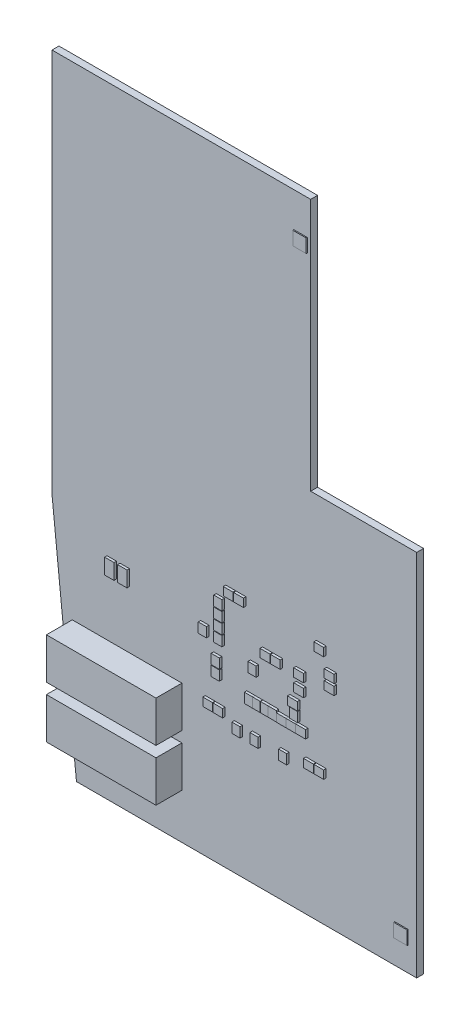
SolidWorks part; units mm, degrees
ref_plane "Front Plane" through (0, 0, 0) normal (0, 0, 1) x (1, 0, 0)
ref_plane "Top Plane" through (0, 0, 0) normal (0, 1, 0) x (1, 0, 0)
ref_plane "Right Plane" through (0, 0, 0) normal (1, 0, 0) x (0, 0, -1)
sketch "Sketch1" plane through (0, 0, 0) normal (0, 0, 1) x (1, 0, 0)
  line L0 (0, 152.4) -> (0, 57.9999)
  line L1 (0, 57.9999) -> (6, 0)
  line L2 (6, 0) -> (89.44, 0)
  line L3 (89.44, 0) -> (89.44, 90.4001)
  line L4 (89.44, 90.4001) -> (63.4401, 90.4001)
  line L5 (63.4401, 90.4001) -> (63.4401, 152.4)
  line L6 (63.4401, 152.4) -> (0, 152.4)
extrude "BOARD" add sketch "Sketch1" along normal blind 1.6977 separate body
ref_plane "Plane1" through (0, 0, 1.6977) normal (0, 0, 1) x (1, 0, 0)
sketch "Sketch2" plane through (0, 0, 0) normal (0, 0, 1) x (1, 0, 0)
  line L0 (68.9999, 30.9999) -> (40.9999, 30.9999)
  line L1 (40.9999, 30.9999) -> (40.9999, 58.9999)
  line L2 (40.9999, 58.9999) -> (68.9999, 58.9999)
  line L3 (68.9999, 58.9999) -> (68.9999, 30.9999)
extrude "PBGA_324P_1MM-1" add sketch "Sketch2" against normal blind 2.5499 separate body
sketch "R2512-1 [0]" plane through (0, 0, 0) normal (0, 0, 1) x (1, 0, 0)
  line L0 (82.9884, 66.3834) -> (82.9884, 74.5866)
  line L1 (82.9884, 74.5866) -> (87.1916, 74.5866)
  line L2 (87.1916, 74.5866) -> (87.1916, 66.3834)
  line L3 (87.1916, 66.3834) -> (82.9884, 66.3834)
sketch "C0805-1 [0]" plane through (0, 0, 0) normal (0, 0, 1) x (1, 0, 0)
  line L0 (70.9516, 70.4276) -> (70.9516, 66.2244)
  line L1 (70.9516, 66.2244) -> (68.7484, 66.2244)
  line L2 (68.7484, 66.2244) -> (68.7484, 70.4276)
  line L3 (68.7484, 70.4276) -> (70.9516, 70.4276)
sketch "Sketch5" plane through (0, 0, 0) normal (0, 0, 1) x (1, 0, 0)
  line L0 (82.3417, 64.6293) -> (75.1383, 64.6293)
  line L1 (75.1383, 64.6293) -> (75.1383, 74.8327)
  line L2 (75.1383, 74.8327) -> (82.3417, 74.8327)
  line L3 (82.3417, 74.8327) -> (82.3417, 64.6293)
extrude "SOT-223-1" add sketch "Sketch5" against normal blind 1.778 separate body
sketch "R1210-1 [0]" plane through (0, 0, 0) normal (0, 0, 1) x (1, 0, 0)
  line L0 (79.4367, 60.5785) -> (74.2333, 60.5785)
  line L1 (74.2333, 60.5785) -> (74.2333, 63.8815)
  line L2 (74.2333, 63.8815) -> (79.4367, 63.8815)
  line L3 (79.4367, 63.8815) -> (79.4367, 60.5785)
sketch "C0805-2 [0]" plane through (0, 0, 0) normal (0, 0, 1) x (1, 0, 0)
  line L0 (79.8134, 63.3316) -> (84.0166, 63.3316)
  line L1 (84.0166, 63.3316) -> (84.0166, 61.1284)
  line L2 (84.0166, 61.1284) -> (79.8134, 61.1284)
  line L3 (79.8134, 61.1284) -> (79.8134, 63.3316)
sketch "Sketch8" plane through (0, 0, 0) normal (0, 0, 1) x (1, 0, 0)
  line L0 (32.0985, 137.3518) -> (44.1018, 137.3518)
  line L1 (44.1018, 137.3518) -> (44.1018, 125.6485)
  line L2 (44.1018, 125.6485) -> (32.0985, 125.6485)
  line L3 (32.0985, 125.6485) -> (32.0985, 137.3518)
extrude "HTSSOP_32P_0_65-1" add sketch "Sketch8" against normal blind 2.65 separate body
sketch "L0805-1 [0]" plane through (0, 0, 1.6977) normal (0, 0, 1) x (1, 0, 0)
  line L0 (43.0116, 26.4734) -> (43.0116, 30.6766)
  line L1 (43.0116, 30.6766) -> (40.8084, 30.6766)
  line L2 (40.8084, 30.6766) -> (40.8084, 26.4734)
  line L3 (40.8084, 26.4734) -> (43.0116, 26.4734)
sketch "L1210-1 [0]" plane through (0, 0, 0) normal (0, 0, 1) x (1, 0, 0)
  line L0 (33.7167, 45.3385) -> (28.5133, 45.3385)
  line L1 (28.5133, 45.3385) -> (28.5133, 48.6415)
  line L2 (28.5133, 48.6415) -> (33.7167, 48.6415)
  line L3 (33.7167, 48.6415) -> (33.7167, 45.3385)
sketch "C0603-1 [0]" plane through (0, 0, 0) normal (0, 0, 1) x (1, 0, 0)
  line L0 (30.1983, 45.3017) -> (33.3017, 45.3017)
  line L1 (33.3017, 45.3017) -> (33.3017, 43.5983)
  line L2 (33.3017, 43.5983) -> (30.1983, 43.5983)
  line L3 (30.1983, 43.5983) -> (30.1983, 45.3017)
sketch "C0603-2 [0]" plane through (0, 0, 0) normal (0, 0, 1) x (1, 0, 0)
  line L0 (30.1983, 43.3967) -> (33.3017, 43.3967)
  line L1 (33.3017, 43.3967) -> (33.3017, 41.6933)
  line L2 (33.3017, 41.6933) -> (30.1983, 41.6933)
  line L3 (30.1983, 41.6933) -> (30.1983, 43.3967)
sketch "C0603-3 [0]" plane through (0, 0, 1.6977) normal (0, 0, 1) x (1, 0, 0)
  line L0 (57.4317, 60.5417) -> (54.3283, 60.5417)
  line L1 (54.3283, 60.5417) -> (54.3283, 58.8383)
  line L2 (54.3283, 58.8383) -> (57.4317, 58.8383)
  line L3 (57.4317, 58.8383) -> (57.4317, 60.5417)
sketch "R0603-1 [0]" plane through (0, 0, 1.6977) normal (0, 0, 1) x (1, 0, 0)
  line L0 (26.4483, 122.1483) -> (29.5516, 122.1483)
  line L1 (29.5516, 122.1483) -> (29.5516, 123.8517)
  line L2 (29.5516, 123.8517) -> (26.4483, 123.8517)
  line L3 (26.4483, 123.8517) -> (26.4483, 122.1483)
sketch "R0603-2 [0]" plane through (0, 0, 1.6977) normal (0, 0, 1) x (1, 0, 0)
  line L0 (34.3517, 137.9484) -> (34.3517, 141.0518)
  line L1 (34.3517, 141.0518) -> (32.6484, 141.0518)
  line L2 (32.6484, 141.0518) -> (32.6484, 137.9484)
  line L3 (32.6484, 137.9484) -> (34.3517, 137.9484)
sketch "R0603-3 [0]" plane through (0, 0, 1.6977) normal (0, 0, 1) x (1, 0, 0)
  line L0 (42.1483, 126.0516) -> (42.1483, 122.9482)
  line L1 (42.1483, 122.9482) -> (43.8516, 122.9482)
  line L2 (43.8516, 122.9482) -> (43.8516, 126.0516)
  line L3 (43.8516, 126.0516) -> (42.1483, 126.0516)
sketch "R0603-4 [0]" plane through (0, 0, 0) normal (0, 0, 1) x (1, 0, 0)
  line L0 (48.0517, 136.6484) -> (44.9483, 136.6484)
  line L1 (44.9483, 136.6484) -> (44.9483, 138.3518)
  line L2 (44.9483, 138.3518) -> (48.0517, 138.3518)
  line L3 (48.0517, 138.3518) -> (48.0517, 136.6484)
sketch "R0603-5 [0]" plane through (0, 0, 0) normal (0, 0, 1) x (1, 0, 0)
  line L0 (41.4917, 35.8417) -> (41.4917, 32.7383)
  line L1 (41.4917, 32.7383) -> (39.7883, 32.7383)
  line L2 (39.7883, 32.7383) -> (39.7883, 35.8417)
  line L3 (39.7883, 35.8417) -> (41.4917, 35.8417)
sketch "L0805-2 [0]" plane through (0, 0, 1.6977) normal (0, 0, 1) x (1, 0, 0)
  line L0 (58.2356, 62.8236) -> (54.0324, 62.8236)
  line L1 (54.0324, 62.8236) -> (54.0324, 60.6204)
  line L2 (54.0324, 60.6204) -> (58.2356, 60.6204)
  line L3 (58.2356, 60.6204) -> (58.2356, 62.8236)
sketch "R0603-6 [0]" plane through (0, 0, 1.6977) normal (0, 0, 1) x (1, 0, 0)
  line L0 (29.5516, 127.8517) -> (26.4483, 127.8517)
  line L1 (26.4483, 127.8517) -> (26.4483, 126.1483)
  line L2 (26.4483, 126.1483) -> (29.5516, 126.1483)
  line L3 (29.5516, 126.1483) -> (29.5516, 127.8517)
sketch "R0603-7 [0]" plane through (0, 0, 1.6977) normal (0, 0, 1) x (1, 0, 0)
  line L0 (29.5516, 129.8517) -> (26.4483, 129.8517)
  line L1 (26.4483, 129.8517) -> (26.4483, 128.1483)
  line L2 (26.4483, 128.1483) -> (29.5516, 128.1483)
  line L3 (29.5516, 128.1483) -> (29.5516, 129.8517)
sketch "R0603-8 [0]" plane through (0, 0, 1.6977) normal (0, 0, 1) x (1, 0, 0)
  line L0 (29.5516, 125.8517) -> (26.4483, 125.8517)
  line L1 (26.4483, 125.8517) -> (26.4483, 124.1483)
  line L2 (26.4483, 124.1483) -> (29.5516, 124.1483)
  line L3 (29.5516, 124.1483) -> (29.5516, 125.8517)
sketch "R0603-9 [0]" plane through (0, 0, 1.6977) normal (0, 0, 1) x (1, 0, 0)
  line L0 (29.5516, 131.8517) -> (26.4483, 131.8517)
  line L1 (26.4483, 131.8517) -> (26.4483, 130.1483)
  line L2 (26.4483, 130.1483) -> (29.5516, 130.1483)
  line L3 (29.5516, 130.1483) -> (29.5516, 131.8517)
sketch "R0603-10 [0]" plane through (0, 0, 1.6977) normal (0, 0, 1) x (1, 0, 0)
  line L0 (29.5516, 135.8516) -> (26.4483, 135.8516)
  line L1 (26.4483, 135.8516) -> (26.4483, 134.1483)
  line L2 (26.4483, 134.1483) -> (29.5516, 134.1483)
  line L3 (29.5516, 134.1483) -> (29.5516, 135.8516)
sketch "C0603-4 [0]" plane through (0, 0, 1.6977) normal (0, 0, 1) x (1, 0, 0)
  line L0 (43.8516, 130.4483) -> (43.8516, 133.5517)
  line L1 (43.8516, 133.5517) -> (42.1483, 133.5517)
  line L2 (42.1483, 133.5517) -> (42.1483, 130.4483)
  line L3 (42.1483, 130.4483) -> (43.8516, 130.4483)
sketch "C0603-5 [0]" plane through (0, 0, 0) normal (0, 0, 1) x (1, 0, 0)
  line L0 (52.1693, 133.3127) -> (55.2727, 133.3127)
  line L1 (55.2727, 133.3127) -> (55.2727, 131.6093)
  line L2 (55.2727, 131.6093) -> (52.1693, 131.6093)
  line L3 (52.1693, 131.6093) -> (52.1693, 133.3127)
sketch "C6032_T-1 [0]" plane through (0, 0, 0) normal (0, 0, 1) x (1, 0, 0)
  line L0 (50.8485, 117.1517) -> (61.1017, 117.1517)
  line L1 (61.1017, 117.1517) -> (61.1017, 111.8984)
  line L2 (61.1017, 111.8984) -> (50.8485, 111.8984)
  line L3 (50.8485, 111.8984) -> (50.8485, 117.1517)
sketch "C0603-6 [0]" plane through (0, 0, 0) normal (0, 0, 1) x (1, 0, 0)
  line L0 (47.3517, 131.5517) -> (47.3517, 128.4483)
  line L1 (47.3517, 128.4483) -> (45.6484, 128.4483)
  line L2 (45.6484, 128.4483) -> (45.6484, 131.5517)
  line L3 (45.6484, 131.5517) -> (47.3517, 131.5517)
sketch "C0603-7 [0]" plane through (0, 0, 0) normal (0, 0, 1) x (1, 0, 0)
  line L0 (46.4482, 126.3515) -> (49.5516, 126.3515)
  line L1 (49.5516, 126.3515) -> (49.5516, 124.6482)
  line L2 (49.5516, 124.6482) -> (46.4482, 124.6482)
  line L3 (46.4482, 124.6482) -> (46.4482, 126.3515)
sketch "SMB-1 [0]" plane through (0, 0, 0) normal (0, 0, 1) x (1, 0, 0)
  line L0 (60.6016, 101.6485) -> (52.3984, 101.6485)
  line L1 (52.3984, 101.6485) -> (52.3984, 106.3516)
  line L2 (52.3984, 106.3516) -> (60.6016, 106.3516)
  line L3 (60.6016, 106.3516) -> (60.6016, 101.6485)
sketch "C0603-8 [0]" plane through (0, 0, 0) normal (0, 0, 1) x (1, 0, 0)
  line L0 (9.6484, 128.9484) -> (9.6484, 132.0518)
  line L1 (9.6484, 132.0518) -> (11.3518, 132.0518)
  line L2 (11.3518, 132.0518) -> (11.3518, 128.9484)
  line L3 (11.3518, 128.9484) -> (9.6484, 128.9484)
sketch "R0603-11 [0]" plane through (0, 0, 1.6977) normal (0, 0, 1) x (1, 0, 0)
  line L0 (26.4483, 136.1483) -> (29.5516, 136.1483)
  line L1 (29.5516, 136.1483) -> (29.5516, 137.8516)
  line L2 (29.5516, 137.8516) -> (26.4483, 137.8516)
  line L3 (26.4483, 137.8516) -> (26.4483, 136.1483)
sketch "C0603-9 [0]" plane through (0, 0, 0) normal (0, 0, 1) x (1, 0, 0)
  line L0 (45.6484, 133.4483) -> (45.6484, 136.5517)
  line L1 (45.6484, 136.5517) -> (47.3517, 136.5517)
  line L2 (47.3517, 136.5517) -> (47.3517, 133.4483)
  line L3 (47.3517, 133.4483) -> (45.6484, 133.4483)
sketch "SMC-1 [0]" plane through (0, 0, 0) normal (0, 0, 1) x (1, 0, 0)
  line L0 (62.6326, 133.6484) -> (52.4294, 133.6484)
  line L1 (52.4294, 133.6484) -> (52.4294, 140.3515)
  line L2 (52.4294, 140.3515) -> (62.6326, 140.3515)
  line L3 (62.6326, 140.3515) -> (62.6326, 133.6484)
sketch "C0603-10 [0]" plane through (0, 0, 1.6977) normal (0, 0, 1) x (1, 0, 0)
  line L0 (34.8516, 130.4483) -> (34.8516, 133.5517)
  line L1 (34.8516, 133.5517) -> (33.1483, 133.5517)
  line L2 (33.1483, 133.5517) -> (33.1483, 130.4483)
  line L3 (33.1483, 130.4483) -> (34.8516, 130.4483)
sketch "R0603-12 [0]" plane through (0, 0, 0) normal (0, 0, 1) x (1, 0, 0)
  line L0 (29.3517, 142.0518) -> (29.3517, 138.9484)
  line L1 (29.3517, 138.9484) -> (27.6484, 138.9484)
  line L2 (27.6484, 138.9484) -> (27.6484, 142.0518)
  line L3 (27.6484, 142.0518) -> (29.3517, 142.0518)
sketch "C0603-11 [0]" plane through (0, 0, 0) normal (0, 0, 1) x (1, 0, 0)
  line L0 (25.6484, 138.9484) -> (25.6484, 142.0518)
  line L1 (25.6484, 142.0518) -> (27.3517, 142.0518)
  line L2 (27.3517, 142.0518) -> (27.3517, 138.9484)
  line L3 (27.3517, 138.9484) -> (25.6484, 138.9484)
sketch "R0603-13 [0]" plane through (0, 0, 0) normal (0, 0, 1) x (1, 0, 0)
  line L0 (33.3517, 142.0518) -> (33.3517, 138.9484)
  line L1 (33.3517, 138.9484) -> (31.6484, 138.9484)
  line L2 (31.6484, 138.9484) -> (31.6484, 142.0518)
  line L3 (31.6484, 142.0518) -> (33.3517, 142.0518)
sketch "C0603-12 [0]" plane through (0, 0, 0) normal (0, 0, 1) x (1, 0, 0)
  line L0 (31.3517, 142.0518) -> (31.3517, 138.9484)
  line L1 (31.3517, 138.9484) -> (29.6484, 138.9484)
  line L2 (29.6484, 138.9484) -> (29.6484, 142.0518)
  line L3 (29.6484, 142.0518) -> (31.3517, 142.0518)
sketch "C0603-13 [0]" plane through (0, 0, 0) normal (0, 0, 1) x (1, 0, 0)
  line L0 (35.3517, 146.5516) -> (35.3517, 143.4483)
  line L1 (35.3517, 143.4483) -> (33.6484, 143.4483)
  line L2 (33.6484, 143.4483) -> (33.6484, 146.5516)
  line L3 (33.6484, 146.5516) -> (35.3517, 146.5516)
sketch "R0603-14 [0]" plane through (0, 0, 0) normal (0, 0, 1) x (1, 0, 0)
  line L0 (34.0083, 41.4917) -> (37.1117, 41.4917)
  line L1 (37.1117, 41.4917) -> (37.1117, 39.7883)
  line L2 (37.1117, 39.7883) -> (34.0083, 39.7883)
  line L3 (34.0083, 39.7883) -> (34.0083, 41.4917)
sketch "R0603-15 [0]" plane through (0, 0, 1.6977) normal (0, 0, 1) x (1, 0, 0)
  line L0 (37.1117, 41.4917) -> (34.0083, 41.4917)
  line L1 (34.0083, 41.4917) -> (34.0083, 39.7883)
  line L2 (34.0083, 39.7883) -> (37.1117, 39.7883)
  line L3 (37.1117, 39.7883) -> (37.1117, 41.4917)
sketch "R0603-16 [0]" plane through (0, 0, 0) normal (0, 0, 1) x (1, 0, 0)
  line L0 (34.0083, 39.5867) -> (37.1117, 39.5867)
  line L1 (37.1117, 39.5867) -> (37.1117, 37.8833)
  line L2 (37.1117, 37.8833) -> (34.0083, 37.8833)
  line L3 (34.0083, 37.8833) -> (34.0083, 39.5867)
sketch "R0603-17 [0]" plane through (0, 0, 0) normal (0, 0, 1) x (1, 0, 0)
  line L0 (37.1117, 35.9783) -> (34.0083, 35.9783)
  line L1 (34.0083, 35.9783) -> (34.0083, 37.6817)
  line L2 (34.0083, 37.6817) -> (37.1117, 37.6817)
  line L3 (37.1117, 37.6817) -> (37.1117, 35.9783)
sketch "R0603-18 [0]" plane through (0, 0, 0) normal (0, 0, 1) x (1, 0, 0)
  line L0 (25.0467, 32.1683) -> (21.9433, 32.1683)
  line L1 (21.9433, 32.1683) -> (21.9433, 33.8717)
  line L2 (21.9433, 33.8717) -> (25.0467, 33.8717)
  line L3 (25.0467, 33.8717) -> (25.0467, 32.1683)
sketch "R0603-19 [0]" plane through (0, 0, 0) normal (0, 0, 1) x (1, 0, 0)
  line L0 (28.2217, 32.1683) -> (25.1183, 32.1683)
  line L1 (25.1183, 32.1683) -> (25.1183, 33.8717)
  line L2 (25.1183, 33.8717) -> (28.2217, 33.8717)
  line L3 (28.2217, 33.8717) -> (28.2217, 32.1683)
sketch "R0603-20 [0]" plane through (0, 0, 0) normal (0, 0, 1) x (1, 0, 0)
  line L0 (25.0467, 35.9783) -> (21.9433, 35.9783)
  line L1 (21.9433, 35.9783) -> (21.9433, 37.6817)
  line L2 (21.9433, 37.6817) -> (25.0467, 37.6817)
  line L3 (25.0467, 37.6817) -> (25.0467, 35.9783)
sketch "R0603-21 [0]" plane through (0, 0, 0) normal (0, 0, 1) x (1, 0, 0)
  line L0 (21.9433, 39.5867) -> (25.0467, 39.5867)
  line L1 (25.0467, 39.5867) -> (25.0467, 37.8833)
  line L2 (25.0467, 37.8833) -> (21.9433, 37.8833)
  line L3 (21.9433, 37.8833) -> (21.9433, 39.5867)
sketch "R0603-22 [0]" plane through (0, 0, 0) normal (0, 0, 1) x (1, 0, 0)
  line L0 (25.0467, 24.5483) -> (21.9433, 24.5483)
  line L1 (21.9433, 24.5483) -> (21.9433, 26.2517)
  line L2 (21.9433, 26.2517) -> (25.0467, 26.2517)
  line L3 (25.0467, 26.2517) -> (25.0467, 24.5483)
sketch "R0603-23 [0]" plane through (0, 0, 0) normal (0, 0, 1) x (1, 0, 0)
  line L0 (21.9433, 24.3467) -> (25.0467, 24.3467)
  line L1 (25.0467, 24.3467) -> (25.0467, 22.6433)
  line L2 (25.0467, 22.6433) -> (21.9433, 22.6433)
  line L3 (21.9433, 22.6433) -> (21.9433, 24.3467)
sketch "R0603-24 [0]" plane through (0, 0, 1.6977) normal (0, 0, 1) x (1, 0, 0)
  line L0 (34.7083, 29.4917) -> (34.7083, 26.3883)
  line L1 (34.7083, 26.3883) -> (36.4117, 26.3883)
  line L2 (36.4117, 26.3883) -> (36.4117, 29.4917)
  line L3 (36.4117, 29.4917) -> (34.7083, 29.4917)
sketch "R0603-25 [0]" plane through (0, 0, 1.6977) normal (0, 0, 1) x (1, 0, 0)
  line L0 (38.3167, 26.3883) -> (38.3167, 29.4917)
  line L1 (38.3167, 29.4917) -> (36.6133, 29.4917)
  line L2 (36.6133, 29.4917) -> (36.6133, 26.3883)
  line L3 (36.6133, 26.3883) -> (38.3167, 26.3883)
sketch "Sketch53" plane through (0, 0, 0) normal (0, 0, 1) x (1, 0, 0)
  line L0 (25.4935, 40.9517) -> (33.6967, 40.9517)
  line L1 (33.6967, 40.9517) -> (33.6967, 35.1485)
  line L2 (33.6967, 35.1485) -> (25.4935, 35.1485)
  line L3 (25.4935, 35.1485) -> (25.4935, 40.9517)
extrude "TSSOP_14P_0_65-1" add sketch "Sketch53" against normal blind 1.1001 separate body
sketch "Sketch54" plane through (0, 0, 0) normal (0, 0, 1) x (1, 0, 0)
  line L0 (25.4935, 30.1567) -> (33.6967, 30.1567)
  line L1 (33.6967, 30.1567) -> (33.6967, 24.3535)
  line L2 (33.6967, 24.3535) -> (25.4935, 24.3535)
  line L3 (25.4935, 24.3535) -> (25.4935, 30.1567)
extrude "TSSOP_14P_0_65-2" add sketch "Sketch54" against normal blind 1.1001 separate body
sketch "R0603-26 [0]" plane through (0, 0, 1.6977) normal (0, 0, 1) x (1, 0, 0)
  line L0 (49.3517, 122.9482) -> (49.3517, 126.0516)
  line L1 (49.3517, 126.0516) -> (47.6484, 126.0516)
  line L2 (47.6484, 126.0516) -> (47.6484, 122.9482)
  line L3 (47.6484, 122.9482) -> (49.3517, 122.9482)
sketch "R0603-27 [0]" plane through (0, 0, 1.6977) normal (0, 0, 1) x (1, 0, 0)
  line L0 (45.9483, 121.1483) -> (49.0517, 121.1483)
  line L1 (49.0517, 121.1483) -> (49.0517, 122.8517)
  line L2 (49.0517, 122.8517) -> (45.9483, 122.8517)
  line L3 (45.9483, 122.8517) -> (45.9483, 121.1483)
sketch "Sketch57" plane through (0, 0, 0) normal (0, 0, 1) x (1, 0, 0)
  line L0 (75.1502, 13.1501) -> (75.1502, 22.8498)
  line L1 (75.1502, 22.8498) -> (86.85, 22.8498)
  line L2 (86.85, 22.8498) -> (86.85, 13.1501)
  line L3 (86.85, 13.1501) -> (75.1502, 13.1501)
extrude "BGA_48P_0_8-1" add sketch "Sketch57" against normal blind 1 separate body
sketch "Sketch58" plane through (0, 0, 0) normal (0, 0, 1) x (1, 0, 0)
  line L0 (86.85, 49.8498) -> (86.85, 40.15)
  line L1 (86.85, 40.15) -> (75.1502, 40.15)
  line L2 (75.1502, 40.15) -> (75.1502, 49.8498)
  line L3 (75.1502, 49.8498) -> (86.85, 49.8498)
extrude "FBGA_48P_0_75_S-1" add sketch "Sketch58" against normal blind 1.1999 separate body
sketch "Sketch59" plane through (0, 0, 0) normal (0, 0, 1) x (1, 0, 0)
  line L0 (87.8502, 38.8501) -> (87.8502, 25.1498)
  line L1 (87.8502, 25.1498) -> (74.15, 25.1498)
  line L2 (74.15, 25.1498) -> (74.15, 38.8501)
  line L3 (74.15, 38.8501) -> (87.8502, 38.8501)
extrude "FBGA_48P_0_75-1" add sketch "Sketch59" against normal blind 1.35 separate body
sketch "Sketch60" plane through (0, 0, 0) normal (0, 0, 1) x (1, 0, 0)
  line L0 (22, 70.0001) -> (22, 84.0001)
  line L1 (22, 84.0001) -> (35.9999, 84.0001)
  line L2 (35.9999, 84.0001) -> (35.9999, 70.0001)
  line L3 (35.9999, 70.0001) -> (22, 70.0001)
extrude "TFBGA_128P_0_8-1" add sketch "Sketch60" against normal blind 1.1999 separate body
sketch "R0603-28 [0]" plane through (0, 0, 0) normal (0, 0, 1) x (1, 0, 0)
  line L0 (35.3433, 65.7583) -> (35.3433, 68.8617)
  line L1 (35.3433, 68.8617) -> (37.0467, 68.8617)
  line L2 (37.0467, 68.8617) -> (37.0467, 65.7583)
  line L3 (37.0467, 65.7583) -> (35.3433, 65.7583)
sketch "Sketch62" plane through (0, 0, 0) normal (0, 0, 1) x (1, 0, 0)
  line L0 (3.0734, 89.3582) -> (3.0734, 97.6376)
  line L1 (3.0734, 97.6376) -> (8.9167, 97.6376)
  line L2 (8.9167, 97.6376) -> (8.9167, 89.3582)
  line L3 (8.9167, 89.3582) -> (3.0734, 89.3582)
extrude "SO8-1" add sketch "Sketch62" against normal blind 1.7501 separate body
sketch "CRY_ABM11B_4P-1 [0]" plane through (0, 0, 0) normal (0, 0, 1) x (1, 0, 0)
  line L0 (31.4096, 85.4644) -> (28.3865, 85.4644)
  line L1 (28.3865, 85.4644) -> (28.3865, 87.9676)
  line L2 (28.3865, 87.9676) -> (31.4096, 87.9676)
  line L3 (31.4096, 87.9676) -> (31.4096, 85.4644)
sketch "C0603-14 [0]" plane through (0, 0, 0) normal (0, 0, 1) x (1, 0, 0)
  line L0 (29.5834, 85.4316) -> (32.6868, 85.4316)
  line L1 (32.6868, 85.4316) -> (32.6868, 83.7283)
  line L2 (32.6868, 83.7283) -> (29.5834, 83.7283)
  line L3 (29.5834, 83.7283) -> (29.5834, 85.4316)
sketch "C0603-15 [0]" plane through (0, 0, 0) normal (0, 0, 1) x (1, 0, 0)
  line L0 (29.5118, 83.7283) -> (26.4084, 83.7283)
  line L1 (26.4084, 83.7283) -> (26.4084, 85.4316)
  line L2 (26.4084, 85.4316) -> (29.5118, 85.4316)
  line L3 (29.5118, 85.4316) -> (29.5118, 83.7283)
sketch "Sketch66" plane through (0, 0, 0) normal (0, 0, 1) x (1, 0, 0)
  line L0 (32.0317, 49.4134) -> (17.0284, 49.4134)
  line L1 (17.0284, 49.4134) -> (17.0284, 63.6166)
  line L2 (17.0284, 63.6166) -> (32.0317, 63.6166)
  line L3 (32.0317, 63.6166) -> (32.0317, 49.4134)
extrude "TQFP_44P_0_8-1" add sketch "Sketch66" against normal blind 1.1999 separate body
sketch "R0603-29 [0]" plane through (0, 0, 0) normal (0, 0, 1) x (1, 0, 0)
  line L0 (53.7583, 65.7583) -> (53.7583, 68.8617)
  line L1 (53.7583, 68.8617) -> (55.4617, 68.8617)
  line L2 (55.4617, 68.8617) -> (55.4617, 65.7583)
  line L3 (55.4617, 65.7583) -> (53.7583, 65.7583)
sketch "Sketch68" plane through (0, 0, 0) normal (0, 0, 1) x (1, 0, 0)
  line L0 (59.7916, 98.6018) -> (59.7916, 90.3224)
  line L1 (59.7916, 90.3224) -> (53.9483, 90.3224)
  line L2 (53.9483, 90.3224) -> (53.9483, 98.6018)
  line L3 (53.9483, 98.6018) -> (59.7916, 98.6018)
extrude "SO8-2" add sketch "Sketch68" against normal blind 1.7501 separate body
sketch "CRY_ABM11B_4P-2 [0]" plane through (0, 0, 0) normal (0, 0, 1) x (1, 0, 0)
  line L0 (52.5856, 84.7644) -> (49.5625, 84.7644)
  line L1 (49.5625, 84.7644) -> (49.5625, 87.2675)
  line L2 (49.5625, 87.2675) -> (52.5856, 87.2675)
  line L3 (52.5856, 87.2675) -> (52.5856, 84.7644)
sketch "R0603-30 [0]" plane through (0, 0, 1.6977) normal (0, 0, 1) x (1, 0, 0)
  line L0 (41.6283, 79.1583) -> (44.7317, 79.1583)
  line L1 (44.7317, 79.1583) -> (44.7317, 80.8617)
  line L2 (44.7317, 80.8617) -> (41.6283, 80.8617)
  line L3 (41.6283, 80.8617) -> (41.6283, 79.1583)
sketch "C0603-16 [0]" plane through (0, 0, 0) normal (0, 0, 1) x (1, 0, 0)
  line L0 (50.7723, 84.9257) -> (53.8757, 84.9257)
  line L1 (53.8757, 84.9257) -> (53.8757, 83.2223)
  line L2 (53.8757, 83.2223) -> (50.7723, 83.2223)
  line L3 (50.7723, 83.2223) -> (50.7723, 84.9257)
sketch "C0603-17 [0]" plane through (0, 0, 0) normal (0, 0, 1) x (1, 0, 0)
  line L0 (50.8277, 83.2223) -> (47.7243, 83.2223)
  line L1 (47.7243, 83.2223) -> (47.7243, 84.9257)
  line L2 (47.7243, 84.9257) -> (50.8277, 84.9257)
  line L3 (50.8277, 84.9257) -> (50.8277, 83.2223)
sketch "C0805-3 [0]" plane through (0, 0, 1.6977) normal (0, 0, 1) x (1, 0, 0)
  line L0 (56.3184, 66.2084) -> (60.5216, 66.2084)
  line L1 (60.5216, 66.2084) -> (60.5216, 68.4116)
  line L2 (60.5216, 68.4116) -> (56.3184, 68.4116)
  line L3 (56.3184, 68.4116) -> (56.3184, 66.2084)
sketch "C0805-4 [0]" plane through (0, 0, 1.6977) normal (0, 0, 1) x (1, 0, 0)
  line L0 (4.8834, 95.4184) -> (9.0866, 95.4184)
  line L1 (9.0866, 95.4184) -> (9.0866, 97.6216)
  line L2 (9.0866, 97.6216) -> (4.8834, 97.6216)
  line L3 (4.8834, 97.6216) -> (4.8834, 95.4184)
sketch "C0805-5 [0]" plane through (0, 0, 1.6977) normal (0, 0, 1) x (1, 0, 0)
  line L0 (24.5966, 84.2584) -> (24.5966, 88.4616)
  line L1 (24.5966, 88.4616) -> (22.3934, 88.4616)
  line L2 (22.3934, 88.4616) -> (22.3934, 84.2584)
  line L3 (22.3934, 84.2584) -> (24.5966, 84.2584)
sketch "C0805-6 [0]" plane through (0, 0, 1.6977) normal (0, 0, 1) x (1, 0, 0)
  line L0 (21.7866, 88.0966) -> (17.5834, 88.0966)
  line L1 (17.5834, 88.0966) -> (17.5834, 85.8934)
  line L2 (17.5834, 85.8934) -> (21.7866, 85.8934)
  line L3 (21.7866, 85.8934) -> (21.7866, 88.0966)
sketch "C0805-7 [0]" plane through (0, 0, 1.6977) normal (0, 0, 1) x (1, 0, 0)
  line L0 (40.8084, 67.5066) -> (40.8084, 63.3034)
  line L1 (40.8084, 63.3034) -> (43.0116, 63.3034)
  line L2 (43.0116, 63.3034) -> (43.0116, 67.5066)
  line L3 (43.0116, 67.5066) -> (40.8084, 67.5066)
sketch "R0603-31 [0]" plane through (0, 0, 1.6977) normal (0, 0, 1) x (1, 0, 0)
  line L0 (41.6283, 77.2533) -> (44.7317, 77.2533)
  line L1 (44.7317, 77.2533) -> (44.7317, 78.9567)
  line L2 (44.7317, 78.9567) -> (41.6283, 78.9567)
  line L3 (41.6283, 78.9567) -> (41.6283, 77.2533)
sketch "Sketch79" plane through (0, 0, 0) normal (0, 0, 1) x (1, 0, 0)
  line L0 (43.9999, 70.0001) -> (43.9999, 84.0001)
  line L1 (43.9999, 84.0001) -> (57.9999, 84.0001)
  line L2 (57.9999, 84.0001) -> (57.9999, 70.0001)
  line L3 (57.9999, 70.0001) -> (43.9999, 70.0001)
extrude "TFBGA_128P_0_8-2" add sketch "Sketch79" against normal blind 1.1999 separate body
sketch "C0805-8 [0]" plane through (0, 0, 1.6977) normal (0, 0, 1) x (1, 0, 0)
  line L0 (57.9816, 92.5416) -> (53.7784, 92.5416)
  line L1 (53.7784, 92.5416) -> (53.7784, 90.3384)
  line L2 (53.7784, 90.3384) -> (57.9816, 90.3384)
  line L3 (57.9816, 90.3384) -> (57.9816, 92.5416)
sketch "C0603-18 [0]" plane through (0, 0, 1.6977) normal (0, 0, 1) x (1, 0, 0)
  line L0 (26.3167, 63.0817) -> (23.2133, 63.0817)
  line L1 (23.2133, 63.0817) -> (23.2133, 61.3783)
  line L2 (23.2133, 61.3783) -> (26.3167, 61.3783)
  line L3 (26.3167, 61.3783) -> (26.3167, 63.0817)
sketch "C0603-19 [0]" plane through (0, 0, 1.6977) normal (0, 0, 1) x (1, 0, 0)
  line L0 (23.2133, 49.9483) -> (26.3167, 49.9483)
  line L1 (26.3167, 49.9483) -> (26.3167, 51.6517)
  line L2 (26.3167, 51.6517) -> (23.2133, 51.6517)
  line L3 (23.2133, 51.6517) -> (23.2133, 49.9483)
sketch "C0603-20 [0]" plane through (0, 0, 1.6977) normal (0, 0, 1) x (1, 0, 0)
  line L0 (26.3167, 64.9867) -> (23.2133, 64.9867)
  line L1 (23.2133, 64.9867) -> (23.2133, 63.2833)
  line L2 (23.2133, 63.2833) -> (26.3167, 63.2833)
  line L3 (26.3167, 63.2833) -> (26.3167, 64.9867)
sketch "C0603-21 [0]" plane through (0, 0, 1.6977) normal (0, 0, 1) x (1, 0, 0)
  line L0 (19.2667, 56.4873) -> (19.2667, 59.5907)
  line L1 (19.2667, 59.5907) -> (17.5633, 59.5907)
  line L2 (17.5633, 59.5907) -> (17.5633, 56.4873)
  line L3 (17.5633, 56.4873) -> (19.2667, 56.4873)
sketch "C3216_T-1 [0]" plane through (0, 0, 0) normal (0, 0, 1) x (1, 0, 0)
  line L0 (19.6235, 71.4157) -> (19.6235, 64.4624)
  line L1 (19.6235, 64.4624) -> (15.6703, 64.4624)
  line L2 (15.6703, 64.4624) -> (15.6703, 71.4157)
  line L3 (15.6703, 71.4157) -> (19.6235, 71.4157)
sketch "R0603-32 [0]" plane through (0, 0, 1.6977) normal (0, 0, 1) x (1, 0, 0)
  line L0 (6.7683, 57.4317) -> (6.7683, 54.3283)
  line L1 (6.7683, 54.3283) -> (8.4717, 54.3283)
  line L2 (8.4717, 54.3283) -> (8.4717, 57.4317)
  line L3 (8.4717, 57.4317) -> (6.7683, 57.4317)
sketch "R0603-33 [0]" plane through (0, 0, 1.6977) normal (0, 0, 1) x (1, 0, 0)
  line L0 (8.4717, 58.1383) -> (8.4717, 61.2417)
  line L1 (8.4717, 61.2417) -> (6.7683, 61.2417)
  line L2 (6.7683, 61.2417) -> (6.7683, 58.1383)
  line L3 (6.7683, 58.1383) -> (8.4717, 58.1383)
sketch "R0603-34 [0]" plane through (0, 0, 1.6977) normal (0, 0, 1) x (1, 0, 0)
  line L0 (6.7683, 65.0517) -> (6.7683, 61.9483)
  line L1 (6.7683, 61.9483) -> (8.4717, 61.9483)
  line L2 (8.4717, 61.9483) -> (8.4717, 65.0517)
  line L3 (8.4717, 65.0517) -> (6.7683, 65.0517)
sketch "R0603-35 [0]" plane through (0, 0, 1.6977) normal (0, 0, 1) x (1, 0, 0)
  line L0 (12.9817, 52.2867) -> (9.8783, 52.2867)
  line L1 (9.8783, 52.2867) -> (9.8783, 50.5833)
  line L2 (9.8783, 50.5833) -> (12.9817, 50.5833)
  line L3 (12.9817, 50.5833) -> (12.9817, 52.2867)
sketch "R0603-36 [0]" plane through (0, 0, 0) normal (0, 0, 1) x (1, 0, 0)
  line L0 (18.7683, 81.4967) -> (21.8717, 81.4967)
  line L1 (21.8717, 81.4967) -> (21.8717, 79.7933)
  line L2 (21.8717, 79.7933) -> (18.7683, 79.7933)
  line L3 (18.7683, 79.7933) -> (18.7683, 81.4967)
sketch "R0603-37 [0]" plane through (0, 0, 0) normal (0, 0, 1) x (1, 0, 0)
  line L0 (18.7683, 79.5917) -> (21.8717, 79.5917)
  line L1 (21.8717, 79.5917) -> (21.8717, 77.8883)
  line L2 (21.8717, 77.8883) -> (18.7683, 77.8883)
  line L3 (18.7683, 77.8883) -> (18.7683, 79.5917)
sketch "C0603-22 [0]" plane through (0, 0, 0) normal (0, 0, 1) x (1, 0, 0)
  line L0 (29.5633, 16.0917) -> (32.6667, 16.0917)
  line L1 (32.6667, 16.0917) -> (32.6667, 14.3883)
  line L2 (32.6667, 14.3883) -> (29.5633, 14.3883)
  line L3 (29.5633, 14.3883) -> (29.5633, 16.0917)
sketch "C0603-23 [0]" plane through (0, 0, 0) normal (0, 0, 1) x (1, 0, 0)
  line L0 (26.8867, 23.1417) -> (26.8867, 20.0383)
  line L1 (26.8867, 20.0383) -> (25.1833, 20.0383)
  line L2 (25.1833, 20.0383) -> (25.1833, 23.1417)
  line L3 (25.1833, 23.1417) -> (26.8867, 23.1417)
sketch "C3528_T-1 [0]" plane through (0, 0, 0) normal (0, 0, 1) x (1, 0, 0)
  line L0 (40.6984, 106.6483) -> (40.6984, 113.6015)
  line L1 (40.6984, 113.6015) -> (45.6016, 113.6015)
  line L2 (45.6016, 113.6015) -> (45.6016, 106.6483)
  line L3 (45.6016, 106.6483) -> (40.6984, 106.6483)
sketch "C3528_T-2 [0]" plane through (0, 0, 0) normal (0, 0, 1) x (1, 0, 0)
  line L0 (37.3517, 100.1984) -> (30.3985, 100.1984)
  line L1 (30.3985, 100.1984) -> (30.3985, 105.1016)
  line L2 (30.3985, 105.1016) -> (37.3517, 105.1016)
  line L3 (37.3517, 105.1016) -> (37.3517, 100.1984)
sketch "C3528_T-3 [0]" plane through (0, 0, 0) normal (0, 0, 1) x (1, 0, 0)
  line L0 (45.6984, 106.6483) -> (45.6984, 113.6015)
  line L1 (45.6984, 113.6015) -> (50.6016, 113.6015)
  line L2 (50.6016, 113.6015) -> (50.6016, 106.6483)
  line L3 (50.6016, 106.6483) -> (45.6984, 106.6483)
sketch "C0603-24 [0]" plane through (0, 0, 0) normal (0, 0, 1) x (1, 0, 0)
  line L0 (31.9484, 113.3516) -> (35.0517, 113.3516)
  line L1 (35.0517, 113.3516) -> (35.0517, 111.6482)
  line L2 (35.0517, 111.6482) -> (31.9484, 111.6482)
  line L3 (31.9484, 111.6482) -> (31.9484, 113.3516)
sketch "R0805-1 [0]" plane through (0, 0, 0) normal (0, 0, 1) x (1, 0, 0)
  line L0 (42.6016, 101.8984) -> (38.3984, 101.8984)
  line L1 (38.3984, 101.8984) -> (38.3984, 104.1016)
  line L2 (38.3984, 104.1016) -> (42.6016, 104.1016)
  line L3 (42.6016, 104.1016) -> (42.6016, 101.8984)
sketch "R0805-2 [0]" plane through (0, 0, 0) normal (0, 0, 1) x (1, 0, 0)
  line L0 (38.3984, 104.3983) -> (38.3984, 108.6015)
  line L1 (38.3984, 108.6015) -> (40.6016, 108.6015)
  line L2 (40.6016, 108.6015) -> (40.6016, 104.3983)
  line L3 (40.6016, 104.3983) -> (38.3984, 104.3983)
sketch "C0603-25 [0]" plane through (0, 0, 0) normal (0, 0, 1) x (1, 0, 0)
  line L0 (38.6484, 108.9482) -> (38.6484, 112.0516)
  line L1 (38.6484, 112.0516) -> (40.3517, 112.0516)
  line L2 (40.3517, 112.0516) -> (40.3517, 108.9482)
  line L3 (40.3517, 108.9482) -> (38.6484, 108.9482)
sketch "SMA-1 [0]" plane through (0, 0, 0) normal (0, 0, 1) x (1, 0, 0)
  line L0 (24.1483, 106.6483) -> (24.1483, 114.3516)
  line L1 (24.1483, 114.3516) -> (27.8516, 114.3516)
  line L2 (27.8516, 114.3516) -> (27.8516, 106.6483)
  line L3 (27.8516, 106.6483) -> (24.1483, 106.6483)
sketch "R0805-3 [0]" plane through (0, 0, 0) normal (0, 0, 1) x (1, 0, 0)
  line L0 (5.3985, 103.8984) -> (5.3985, 108.1016)
  line L1 (5.3985, 108.1016) -> (7.6017, 108.1016)
  line L2 (7.6017, 108.1016) -> (7.6017, 103.8984)
  line L3 (7.6017, 103.8984) -> (5.3985, 103.8984)
sketch "C3528_T-4 [0]" plane through (0, 0, 0) normal (0, 0, 1) x (1, 0, 0)
  line L0 (24.3017, 106.8517) -> (24.3017, 99.8985)
  line L1 (24.3017, 99.8985) -> (19.3985, 99.8985)
  line L2 (19.3985, 99.8985) -> (19.3985, 106.8517)
  line L3 (19.3985, 106.8517) -> (24.3017, 106.8517)
sketch "C3528_T-5 [0]" plane through (0, 0, 0) normal (0, 0, 1) x (1, 0, 0)
  line L0 (28.8016, 106.8517) -> (28.8016, 99.8985)
  line L1 (28.8016, 99.8985) -> (23.8984, 99.8985)
  line L2 (23.8984, 99.8985) -> (23.8984, 106.8517)
  line L3 (23.8984, 106.8517) -> (28.8016, 106.8517)
sketch "C3528_T-6 [0]" plane through (0, 0, 0) normal (0, 0, 1) x (1, 0, 0)
  line L0 (9.6985, 107.6482) -> (9.6985, 114.6015)
  line L1 (9.6985, 114.6015) -> (14.6017, 114.6015)
  line L2 (14.6017, 114.6015) -> (14.6017, 107.6482)
  line L3 (14.6017, 107.6482) -> (9.6985, 107.6482)
sketch "Sketch106" plane through (0, 0, 0) normal (0, 0, 1) x (1, 0, 0)
  line L0 (38.1218, 105.8583) -> (29.8425, 105.8583)
  line L1 (29.8425, 105.8583) -> (29.8425, 111.7016)
  line L2 (29.8425, 111.7016) -> (38.1218, 111.7016)
  line L3 (38.1218, 111.7016) -> (38.1218, 105.8583)
extrude "SO8-3" add sketch "Sketch106" against normal blind 1.7501 separate body
sketch "R0805-4 [0]" plane through (0, 0, 0) normal (0, 0, 1) x (1, 0, 0)
  line L0 (9.6017, 101.3983) -> (5.3985, 101.3983)
  line L1 (5.3985, 101.3983) -> (5.3985, 103.6015)
  line L2 (5.3985, 103.6015) -> (9.6017, 103.6015)
  line L3 (9.6017, 103.6015) -> (9.6017, 101.3983)
sketch "R0805-5 [0]" plane through (0, 0, 0) normal (0, 0, 1) x (1, 0, 0)
  line L0 (19.1016, 105.1016) -> (19.1016, 100.8985)
  line L1 (19.1016, 100.8985) -> (16.8984, 100.8985)
  line L2 (16.8984, 100.8985) -> (16.8984, 105.1016)
  line L3 (16.8984, 105.1016) -> (19.1016, 105.1016)
sketch "C3528_T-7 [0]" plane through (0, 0, 0) normal (0, 0, 1) x (1, 0, 0)
  line L0 (4.6985, 107.6482) -> (4.6985, 114.6015)
  line L1 (4.6985, 114.6015) -> (9.6017, 114.6015)
  line L2 (9.6017, 114.6015) -> (9.6017, 107.6482)
  line L3 (9.6017, 107.6482) -> (4.6985, 107.6482)
sketch "C0603-26 [0]" plane through (0, 0, 1.6977) normal (0, 0, 1) x (1, 0, 0)
  line L0 (7.1483, 138.5517) -> (7.1483, 135.4483)
  line L1 (7.1483, 135.4483) -> (8.8516, 135.4483)
  line L2 (8.8516, 135.4483) -> (8.8516, 138.5517)
  line L3 (8.8516, 138.5517) -> (7.1483, 138.5517)
sketch "R0603-38 [0]" plane through (0, 0, 1.6977) normal (0, 0, 1) x (1, 0, 0)
  line L0 (31.5333, 40.9217) -> (31.5333, 37.8183)
  line L1 (31.5333, 37.8183) -> (33.2367, 37.8183)
  line L2 (33.2367, 37.8183) -> (33.2367, 40.9217)
  line L3 (33.2367, 40.9217) -> (31.5333, 40.9217)
sketch "R0603-39 [0]" plane through (0, 0, 0) normal (0, 0, 1) x (1, 0, 0)
  line L0 (25.0467, 39.7883) -> (21.9433, 39.7883)
  line L1 (21.9433, 39.7883) -> (21.9433, 41.4917)
  line L2 (21.9433, 41.4917) -> (25.0467, 41.4917)
  line L3 (25.0467, 41.4917) -> (25.0467, 39.7883)
sketch "R0603-40 [0]" plane through (0, 0, 0) normal (0, 0, 1) x (1, 0, 0)
  line L0 (25.0467, 26.4533) -> (21.9433, 26.4533)
  line L1 (21.9433, 26.4533) -> (21.9433, 28.1567)
  line L2 (21.9433, 28.1567) -> (25.0467, 28.1567)
  line L3 (25.0467, 28.1567) -> (25.0467, 26.4533)
sketch "R0603-41 [0]" plane through (0, 0, 0) normal (0, 0, 1) x (1, 0, 0)
  line L0 (31.5333, 30.8333) -> (31.5333, 33.9367)
  line L1 (31.5333, 33.9367) -> (33.2367, 33.9367)
  line L2 (33.2367, 33.9367) -> (33.2367, 30.8333)
  line L3 (33.2367, 30.8333) -> (31.5333, 30.8333)
sketch "R0603-42 [0]" plane through (0, 0, 1.6977) normal (0, 0, 1) x (1, 0, 0)
  line L0 (25.8183, 38.3817) -> (25.8183, 35.2783)
  line L1 (25.8183, 35.2783) -> (27.5217, 35.2783)
  line L2 (27.5217, 35.2783) -> (27.5217, 38.3817)
  line L3 (27.5217, 38.3817) -> (25.8183, 38.3817)
sketch "C0603-27 [0]" plane through (0, 0, 0) normal (0, 0, 1) x (1, 0, 0)
  line L0 (9.3518, 107.5517) -> (9.3518, 104.4484)
  line L1 (9.3518, 104.4484) -> (7.6484, 104.4484)
  line L2 (7.6484, 104.4484) -> (7.6484, 107.5517)
  line L3 (7.6484, 107.5517) -> (9.3518, 107.5517)
sketch "R0603-43 [0]" plane through (0, 0, 0) normal (0, 0, 1) x (1, 0, 0)
  line L0 (29.6283, 30.8333) -> (29.6283, 33.9367)
  line L1 (29.6283, 33.9367) -> (31.3317, 33.9367)
  line L2 (31.3317, 33.9367) -> (31.3317, 30.8333)
  line L3 (31.3317, 30.8333) -> (29.6283, 30.8333)
sketch "R0603-44 [0]" plane through (0, 0, 1.6977) normal (0, 0, 1) x (1, 0, 0)
  line L0 (29.4267, 35.2783) -> (29.4267, 38.3817)
  line L1 (29.4267, 38.3817) -> (27.7233, 38.3817)
  line L2 (27.7233, 38.3817) -> (27.7233, 35.2783)
  line L3 (27.7233, 35.2783) -> (29.4267, 35.2783)
sketch "CRY_4P_ASDMB-1 [0]" plane through (0, 0, 0) normal (0, 0, 1) x (1, 0, 0)
  line L0 (36.2255, 45.0357) -> (39.8287, 45.0357)
  line L1 (39.8287, 45.0357) -> (39.8287, 41.8323)
  line L2 (39.8287, 41.8323) -> (36.2255, 41.8323)
  line L3 (36.2255, 41.8323) -> (36.2255, 45.0357)
sketch "R0603-45 [0]" plane through (0, 0, 0) normal (0, 0, 1) x (1, 0, 0)
  line L0 (30.6967, 23.1417) -> (30.6967, 20.0383)
  line L1 (30.6967, 20.0383) -> (28.9933, 20.0383)
  line L2 (28.9933, 20.0383) -> (28.9933, 23.1417)
  line L3 (28.9933, 23.1417) -> (30.6967, 23.1417)
sketch "R0603-46 [0]" plane through (0, 0, 0) normal (0, 0, 1) x (1, 0, 0)
  line L0 (29.5633, 17.9967) -> (32.6667, 17.9967)
  line L1 (32.6667, 17.9967) -> (32.6667, 16.2933)
  line L2 (32.6667, 16.2933) -> (29.5633, 16.2933)
  line L3 (29.5633, 16.2933) -> (29.5633, 17.9967)
sketch "R0603-47 [0]" plane through (0, 0, 0) normal (0, 0, 1) x (1, 0, 0)
  line L0 (25.0467, 34.0733) -> (21.9433, 34.0733)
  line L1 (21.9433, 34.0733) -> (21.9433, 35.7767)
  line L2 (21.9433, 35.7767) -> (25.0467, 35.7767)
  line L3 (25.0467, 35.7767) -> (25.0467, 34.0733)
sketch "C0603-28 [0]" plane through (0, 0, 0) normal (0, 0, 1) x (1, 0, 0)
  line L0 (23.6484, 144.9484) -> (23.6484, 148.0518)
  line L1 (23.6484, 148.0518) -> (25.3517, 148.0518)
  line L2 (25.3517, 148.0518) -> (25.3517, 144.9484)
  line L3 (25.3517, 144.9484) -> (23.6484, 144.9484)
sketch "C0603-29 [0]" plane through (0, 0, 0) normal (0, 0, 1) x (1, 0, 0)
  line L0 (21.8516, 124.0516) -> (21.8516, 120.9482)
  line L1 (21.8516, 120.9482) -> (20.1483, 120.9482)
  line L2 (20.1483, 120.9482) -> (20.1483, 124.0516)
  line L3 (20.1483, 124.0516) -> (21.8516, 124.0516)
sketch "C0603-30 [0]" plane through (0, 0, 0) normal (0, 0, 1) x (1, 0, 0)
  line L0 (29.6484, 131.9484) -> (29.6484, 135.0518)
  line L1 (29.6484, 135.0518) -> (31.3517, 135.0518)
  line L2 (31.3517, 135.0518) -> (31.3517, 131.9484)
  line L3 (31.3517, 131.9484) -> (29.6484, 131.9484)
sketch "C3216_T-2 [0]" plane through (0, 0, 0) normal (0, 0, 1) x (1, 0, 0)
  line L0 (25.1485, 129.6485) -> (25.1485, 136.6017)
  line L1 (25.1485, 136.6017) -> (29.1018, 136.6017)
  line L2 (29.1018, 136.6017) -> (29.1018, 129.6485)
  line L3 (29.1018, 129.6485) -> (25.1485, 129.6485)
sketch "L0805-3 [0]" plane through (0, 0, 0) normal (0, 0, 1) x (1, 0, 0)
  line L0 (24.1016, 116.3983) -> (19.8984, 116.3983)
  line L1 (19.8984, 116.3983) -> (19.8984, 118.6015)
  line L2 (19.8984, 118.6015) -> (24.1016, 118.6015)
  line L3 (24.1016, 118.6015) -> (24.1016, 116.3983)
sketch "L0805-4 [0]" plane through (0, 0, 0) normal (0, 0, 1) x (1, 0, 0)
  line L0 (11.3985, 120.8984) -> (11.3985, 125.1016)
  line L1 (11.3985, 125.1016) -> (13.6017, 125.1016)
  line L2 (13.6017, 125.1016) -> (13.6017, 120.8984)
  line L3 (13.6017, 120.8984) -> (11.3985, 120.8984)
sketch "C3216_T-3 [0]" plane through (0, 0, 0) normal (0, 0, 1) x (1, 0, 0)
  line L0 (11.8516, 122.8517) -> (11.8516, 115.8984)
  line L1 (11.8516, 115.8984) -> (7.8984, 115.8984)
  line L2 (7.8984, 115.8984) -> (7.8984, 122.8517)
  line L3 (7.8984, 122.8517) -> (11.8516, 122.8517)
sketch "L0805-5 [0]" plane through (0, 0, 0) normal (0, 0, 1) x (1, 0, 0)
  line L0 (6.8984, 125.1016) -> (11.1016, 125.1016)
  line L1 (11.1016, 125.1016) -> (11.1016, 122.8984)
  line L2 (11.1016, 122.8984) -> (6.8984, 122.8984)
  line L3 (6.8984, 122.8984) -> (6.8984, 125.1016)
sketch "C3216_T-4 [0]" plane through (0, 0, 0) normal (0, 0, 1) x (1, 0, 0)
  line L0 (8.3515, 122.8517) -> (8.3515, 115.8984)
  line L1 (8.3515, 115.8984) -> (4.3983, 115.8984)
  line L2 (4.3983, 115.8984) -> (4.3983, 122.8517)
  line L3 (4.3983, 122.8517) -> (8.3515, 122.8517)
sketch "R1210-2 [0]" plane through (0, 0, 0) normal (0, 0, 1) x (1, 0, 0)
  line L0 (68.3265, 72.8327) -> (68.3265, 67.6293)
  line L1 (68.3265, 67.6293) -> (65.0235, 67.6293)
  line L2 (65.0235, 67.6293) -> (65.0235, 72.8327)
  line L3 (65.0235, 72.8327) -> (68.3265, 72.8327)
sketch "R1210-3 [0]" plane through (0, 0, 0) normal (0, 0, 1) x (1, 0, 0)
  line L0 (71.3735, 65.7243) -> (71.3735, 70.9277)
  line L1 (71.3735, 70.9277) -> (74.6765, 70.9277)
  line L2 (74.6765, 70.9277) -> (74.6765, 65.7243)
  line L3 (74.6765, 65.7243) -> (71.3735, 65.7243)
sketch "C0805-9 [0]" plane through (0, 0, 0) normal (0, 0, 1) x (1, 0, 0)
  line L0 (64.5734, 66.8876) -> (68.7766, 66.8876)
  line L1 (68.7766, 66.8876) -> (68.7766, 64.6844)
  line L2 (68.7766, 64.6844) -> (64.5734, 64.6844)
  line L3 (64.5734, 64.6844) -> (64.5734, 66.8876)
sketch "C0805-10 [0]" plane through (0, 0, 0) normal (0, 0, 1) x (1, 0, 0)
  line L0 (14.1016, 108.1016) -> (14.1016, 103.8984)
  line L1 (14.1016, 103.8984) -> (11.8984, 103.8984)
  line L2 (11.8984, 103.8984) -> (11.8984, 108.1016)
  line L3 (11.8984, 108.1016) -> (14.1016, 108.1016)
sketch "C0603-31 [0]" plane through (0, 0, 0) normal (0, 0, 1) x (1, 0, 0)
  line L0 (62.5117, 58.8383) -> (59.4083, 58.8383)
  line L1 (59.4083, 58.8383) -> (59.4083, 60.5417)
  line L2 (59.4083, 60.5417) -> (62.5117, 60.5417)
  line L3 (62.5117, 60.5417) -> (62.5117, 58.8383)
sketch "R0603-48 [0]" plane through (0, 0, 0) normal (0, 0, 1) x (1, 0, 0)
  line L0 (62.5117, 60.7433) -> (59.4083, 60.7433)
  line L1 (59.4083, 60.7433) -> (59.4083, 62.4467)
  line L2 (59.4083, 62.4467) -> (62.5117, 62.4467)
  line L3 (62.5117, 62.4467) -> (62.5117, 60.7433)
sketch "C0603-32 [0]" plane through (0, 0, 1.6977) normal (0, 0, 1) x (1, 0, 0)
  line L0 (28.9933, 54.8917) -> (28.9933, 51.7883)
  line L1 (28.9933, 51.7883) -> (30.6967, 51.7883)
  line L2 (30.6967, 51.7883) -> (30.6967, 54.8917)
  line L3 (30.6967, 54.8917) -> (28.9933, 54.8917)
sketch "C0805-11 [0]" plane through (0, 0, 0) normal (0, 0, 1) x (1, 0, 0)
  line L0 (50.1015, 131.6017) -> (50.1015, 127.3985)
  line L1 (50.1015, 127.3985) -> (47.8983, 127.3985)
  line L2 (47.8983, 127.3985) -> (47.8983, 131.6017)
  line L3 (47.8983, 131.6017) -> (50.1015, 131.6017)
sketch "Sketch140" plane through (0, 0, 0) normal (0, 0, 1) x (1, 0, 0)
  line L0 (32.1328, 48.5717) -> (32.1328, 57.5419)
  line L1 (32.1328, 57.5419) -> (35.987, 57.5419)
  line L2 (35.987, 57.5419) -> (35.987, 48.5717)
  line L3 (35.987, 48.5717) -> (32.1328, 48.5717)
extrude "TSSOP_8P_0_65-1" add sketch "Sketch140" against normal blind 1.1999 separate body
sketch "R0805-6 [0]" plane through (0, 0, 0) normal (0, 0, 1) x (1, 0, 0)
  line L0 (37.9034, 38.5666) -> (42.1066, 38.5666)
  line L1 (42.1066, 38.5666) -> (42.1066, 36.3634)
  line L2 (42.1066, 36.3634) -> (37.9034, 36.3634)
  line L3 (37.9034, 36.3634) -> (37.9034, 38.5666)
sketch "R0603-49 [0]" plane through (0, 0, 1.6977) normal (0, 0, 1) x (1, 0, 0)
  line L0 (81.4967, 78.4583) -> (81.4967, 81.5617)
  line L1 (81.4967, 81.5617) -> (79.7933, 81.5617)
  line L2 (79.7933, 81.5617) -> (79.7933, 78.4583)
  line L3 (79.7933, 78.4583) -> (81.4967, 78.4583)
sketch "R0603-50 [0]" plane through (0, 0, 1.6977) normal (0, 0, 1) x (1, 0, 0)
  line L0 (77.8883, 81.5617) -> (77.8883, 78.4583)
  line L1 (77.8883, 78.4583) -> (79.5917, 78.4583)
  line L2 (79.5917, 78.4583) -> (79.5917, 81.5617)
  line L3 (79.5917, 81.5617) -> (77.8883, 81.5617)
sketch "R0603-51 [0]" plane through (0, 0, 1.6977) normal (0, 0, 1) x (1, 0, 0)
  line L0 (84.1116, 83.8032) -> (84.1116, 86.9066)
  line L1 (84.1116, 86.9066) -> (82.4083, 86.9066)
  line L2 (82.4083, 86.9066) -> (82.4083, 83.8032)
  line L3 (82.4083, 83.8032) -> (84.1116, 83.8032)
sketch "R0603-52 [0]" plane through (0, 0, 1.6977) normal (0, 0, 1) x (1, 0, 0)
  line L0 (84.4083, 86.9066) -> (84.4083, 83.8032)
  line L1 (84.4083, 83.8032) -> (86.1116, 83.8032)
  line L2 (86.1116, 83.8032) -> (86.1116, 86.9066)
  line L3 (86.1116, 86.9066) -> (84.4083, 86.9066)
sketch "MH_3_55MM-1 [0]" plane through (0, 0, 1.6977) normal (0, 0, 1) x (1, 0, 0)
  line L0 (2.5029, 143.4028) -> (8.4973, 143.4028)
  line L1 (8.4973, 143.4028) -> (8.4973, 149.3972)
  line L2 (8.4973, 149.3972) -> (2.5029, 149.3972)
  line L3 (2.5029, 149.3972) -> (2.5029, 143.4028)
sketch "MH_3_55MM-2 [0]" plane through (0, 0, 1.6977) normal (0, 0, 1) x (1, 0, 0)
  line L0 (7.0028, 3.0028) -> (12.9972, 3.0028)
  line L1 (12.9972, 3.0028) -> (12.9972, 8.9972)
  line L2 (12.9972, 8.9972) -> (7.0028, 8.9972)
  line L3 (7.0028, 8.9972) -> (7.0028, 3.0028)
sketch "MH_3_55MM-3 [0]" plane through (0, 0, 1.6977) normal (0, 0, 1) x (1, 0, 0)
  line L0 (76.4428, 3.0028) -> (82.4372, 3.0028)
  line L1 (82.4372, 3.0028) -> (82.4372, 8.9972)
  line L2 (82.4372, 8.9972) -> (76.4428, 8.9972)
  line L3 (76.4428, 8.9972) -> (76.4428, 3.0028)
sketch "MH_3_55MM-4 [0]" plane through (0, 0, 1.6977) normal (0, 0, 1) x (1, 0, 0)
  line L0 (54.5028, 143.4028) -> (60.4972, 143.4028)
  line L1 (60.4972, 143.4028) -> (60.4972, 149.3972)
  line L2 (60.4972, 149.3972) -> (54.5028, 149.3972)
  line L3 (54.5028, 149.3972) -> (54.5028, 143.4028)
sketch "Sketch150" plane through (0, 0, 0) normal (0, 0, 1) x (1, 0, 0)
  line L0 (74.0867, 12.8567) -> (74.0867, 4.4033)
  line L1 (74.0867, 4.4033) -> (66.6834, 4.4033)
  line L2 (66.6834, 4.4033) -> (66.6834, 12.8567)
  line L3 (66.6834, 12.8567) -> (74.0867, 12.8567)
extrude "TSSOP_20_0_65-1" add sketch "Sketch150" against normal blind 1.1999 separate body
sketch "Sketch151" plane through (0, 0, 0) normal (0, 0, 1) x (1, 0, 0)
  line L0 (25.4533, 12.9083) -> (25.4533, 19.6116)
  line L1 (25.4533, 19.6116) -> (29.1567, 19.6116)
  line L2 (29.1567, 19.6116) -> (29.1567, 12.9083)
  line L3 (29.1567, 12.9083) -> (25.4533, 12.9083)
extrude "MSOP_10P_0_5-1" add sketch "Sketch151" against normal blind 1.1001 separate body
sketch "C0402-1 [0]" plane through (0, 0, 0) normal (0, 0, 1) x (1, 0, 0)
  line L0 (49.0266, 105.3935) -> (46.2234, 105.3935)
  line L1 (46.2234, 105.3935) -> (46.2234, 106.6965)
  line L2 (46.2234, 106.6965) -> (49.0266, 106.6965)
  line L3 (49.0266, 106.6965) -> (49.0266, 105.3935)
sketch "C0402-2 [0]" plane through (0, 0, 1.6977) normal (0, 0, 1) x (1, 0, 0)
  line L0 (77.4746, 18.6855) -> (74.6714, 18.6855)
  line L1 (74.6714, 18.6855) -> (74.6714, 17.3825)
  line L2 (74.6714, 17.3825) -> (77.4746, 17.3825)
  line L3 (77.4746, 17.3825) -> (77.4746, 18.6855)
sketch "C0402-3 [0]" plane through (0, 0, 1.6977) normal (0, 0, 1) x (1, 0, 0)
  line L0 (79.4974, 41.2585) -> (82.3006, 41.2585)
  line L1 (82.3006, 41.2585) -> (82.3006, 42.5615)
  line L2 (82.3006, 42.5615) -> (79.4974, 42.5615)
  line L3 (79.4974, 42.5615) -> (79.4974, 41.2585)
sketch "C0402-4 [0]" plane through (0, 0, 1.6977) normal (0, 0, 1) x (1, 0, 0)
  line L0 (82.3006, 48.6575) -> (79.4974, 48.6575)
  line L1 (79.4974, 48.6575) -> (79.4974, 47.3545)
  line L2 (79.4974, 47.3545) -> (82.3006, 47.3545)
  line L3 (82.3006, 47.3545) -> (82.3006, 48.6575)
sketch "C0402-5 [0]" plane through (0, 0, 1.6977) normal (0, 0, 1) x (1, 0, 0)
  line L0 (82.4276, 35.7035) -> (79.6244, 35.7035)
  line L1 (79.6244, 35.7035) -> (79.6244, 34.4005)
  line L2 (79.6244, 34.4005) -> (82.4276, 34.4005)
  line L3 (82.4276, 34.4005) -> (82.4276, 35.7035)
sketch "C0402-6 [0]" plane through (0, 0, 1.6977) normal (0, 0, 1) x (1, 0, 0)
  line L0 (79.6125, 29.3416) -> (79.6125, 26.5384)
  line L1 (79.6125, 26.5384) -> (80.9155, 26.5384)
  line L2 (80.9155, 26.5384) -> (80.9155, 29.3416)
  line L3 (80.9155, 29.3416) -> (79.6125, 29.3416)
sketch "C0402-7 [0]" plane through (0, 0, 0) normal (0, 0, 1) x (1, 0, 0)
  line L0 (13.1516, 120.4016) -> (13.1516, 117.5984)
  line L1 (13.1516, 117.5984) -> (11.8486, 117.5984)
  line L2 (11.8486, 117.5984) -> (11.8486, 120.4016)
  line L3 (11.8486, 120.4016) -> (13.1516, 120.4016)
sketch "C0402-8 [0]" plane through (0, 0, 0) normal (0, 0, 1) x (1, 0, 0)
  line L0 (4.1516, 120.9015) -> (4.1516, 118.0983)
  line L1 (4.1516, 118.0983) -> (2.8486, 118.0983)
  line L2 (2.8486, 118.0983) -> (2.8486, 120.9015)
  line L3 (2.8486, 120.9015) -> (4.1516, 120.9015)
sketch "C0402-9 [0]" plane through (0, 0, 1.6977) normal (0, 0, 1) x (1, 0, 0)
  line L0 (45.8485, 125.9014) -> (45.8485, 123.0983)
  line L1 (45.8485, 123.0983) -> (47.1515, 123.0983)
  line L2 (47.1515, 123.0983) -> (47.1515, 125.9014)
  line L3 (47.1515, 125.9014) -> (45.8485, 125.9014)
sketch "C0402-10 [0]" plane through (0, 0, 1.6977) normal (0, 0, 1) x (1, 0, 0)
  line L0 (34.1584, 55.8635) -> (36.9616, 55.8635)
  line L1 (36.9616, 55.8635) -> (36.9616, 57.1665)
  line L2 (36.9616, 57.1665) -> (34.1584, 57.1665)
  line L3 (34.1584, 57.1665) -> (34.1584, 55.8635)
sketch "C0402-11 [0]" plane through (0, 0, 1.6977) normal (0, 0, 1) x (1, 0, 0)
  line L0 (42.3484, 130.4016) -> (42.3484, 127.5984)
  line L1 (42.3484, 127.5984) -> (43.6514, 127.5984)
  line L2 (43.6514, 127.5984) -> (43.6514, 130.4016)
  line L3 (43.6514, 130.4016) -> (42.3484, 130.4016)
sketch "C0603-33 [0]" plane through (0, 0, 1.6977) normal (0, 0, 1) x (1, 0, 0)
  line L0 (30.6967, 20.8003) -> (30.6967, 23.9037)
  line L1 (30.6967, 23.9037) -> (28.9933, 23.9037)
  line L2 (28.9933, 23.9037) -> (28.9933, 20.8003)
  line L3 (28.9933, 20.8003) -> (30.6967, 20.8003)
sketch "Sketch164" plane through (0, 0, 0) normal (0, 0, 1) x (1, 0, 0)
  line L0 (10.5385, 99.3216) -> (52.7416, 99.3216)
  line L1 (52.7416, 99.3216) -> (52.7416, 90.3183)
  line L2 (52.7416, 90.3183) -> (10.5385, 90.3183)
  line L3 (10.5385, 90.3183) -> (10.5385, 99.3216)
extrude "CON_80P_0_8MM_QSE_SOC-1" add sketch "Sketch164" against normal blind 3.048 separate body
sketch "Sketch165" plane through (0, 0, 0) normal (0, 0, 1) x (1, 0, 0)
  line L0 (64.8216, 2.1984) -> (22.6184, 2.1984)
  line L1 (22.6184, 2.1984) -> (22.6184, 11.2017)
  line L2 (22.6184, 11.2017) -> (64.8216, 11.2017)
  line L3 (64.8216, 11.2017) -> (64.8216, 2.1984)
extrude "CON_80P_0_8MM_QSE_SOC-2" add sketch "Sketch165" against normal blind 3.048 separate body
sketch "IND_IHLP2525-1 [0]" plane through (0, 0, 0) normal (0, 0, 1) x (1, 0, 0)
  line L0 (23.5204, 106.4514) -> (15.8496, 106.4514)
  line L1 (15.8496, 106.4514) -> (15.8496, 113.2586)
  line L2 (15.8496, 113.2586) -> (23.5204, 113.2586)
  line L3 (23.5204, 113.2586) -> (23.5204, 106.4514)
sketch "IND_IHLP3232D-1 [0]" plane through (0, 0, 0) normal (0, 0, 1) x (1, 0, 0)
  line L0 (42.0804, 138.8184) -> (42.0804, 149.1816)
  line L1 (42.0804, 149.1816) -> (50.9196, 149.1816)
  line L2 (50.9196, 149.1816) -> (50.9196, 138.8184)
  line L3 (50.9196, 138.8184) -> (42.0804, 138.8184)
sketch "IND_IHLP2525-2 [0]" plane through (0, 0, 0) normal (0, 0, 1) x (1, 0, 0)
  line L0 (52.6646, 124.4036) -> (60.3354, 124.4036)
  line L1 (60.3354, 124.4036) -> (60.3354, 117.5964)
  line L2 (60.3354, 117.5964) -> (52.6646, 117.5964)
  line L3 (52.6646, 117.5964) -> (52.6646, 124.4036)
sketch "IND_IHLP2020-1 [0]" plane through (0, 0, 0) normal (0, 0, 1) x (1, 0, 0)
  line L0 (26.3759, 148.5227) -> (32.6243, 148.5227)
  line L1 (32.6243, 148.5227) -> (32.6243, 142.4775)
  line L2 (32.6243, 142.4775) -> (26.3759, 142.4775)
  line L3 (26.3759, 142.4775) -> (26.3759, 148.5227)
sketch "Sketch170" plane through (0, 0, 0) normal (0, 0, 1) x (1, 0, 0)
  line L0 (0.6984, 51.2575) -> (-0.2903, 65.3961)
  line L1 (-0.2903, 65.3961) -> (13.8484, 66.3848)
  line L2 (13.8484, 66.3848) -> (14.837, 52.2461)
  line L3 (14.837, 52.2461) -> (0.6984, 51.2575)
extrude "CON_10P_100_RA-1" add sketch "Sketch170" against normal blind 4.826 separate body
sketch "Sketch171" plane through (0, 0, 0) normal (0, 0, 1) x (1, 0, 0)
  line L0 (-0.1016, 67.8434) -> (-0.1016, 87.7316)
  line L1 (-0.1016, 87.7316) -> (14.0716, 87.7316)
  line L2 (14.0716, 87.7316) -> (14.0716, 67.8434)
  line L3 (14.0716, 67.8434) -> (-0.1016, 67.8434)
extrude "CON_14P_100_RA-1" add sketch "Sketch171" against normal blind 4.826 separate body
sketch "Sketch172" plane through (0, 0, 0) normal (0, 0, 1) x (1, 0, 0)
  line L0 (36.6484, 116.1484) -> (36.6484, 123.8517)
  line L1 (36.6484, 123.8517) -> (50.8516, 123.8517)
  line L2 (50.8516, 123.8517) -> (50.8516, 116.1484)
  line L3 (50.8516, 116.1484) -> (36.6484, 116.1484)
extrude "DPAK-1" add sketch "Sketch172" against normal blind 2.54 separate body
sketch "Sketch173" plane through (0, 0, 0) normal (0, 0, 1) x (1, 0, 0)
  line L0 (25.3517, 126.6485) -> (17.6484, 126.6485)
  line L1 (17.6484, 126.6485) -> (17.6484, 140.8516)
  line L2 (17.6484, 140.8516) -> (25.3517, 140.8516)
  line L3 (25.3517, 140.8516) -> (25.3517, 126.6485)
extrude "DPAK-2" add sketch "Sketch173" against normal blind 2.54 separate body
sketch "Sketch174" plane through (0, 0, 0) normal (0, 0, 1) x (1, 0, 0)
  line L0 (86.1017, 78.1583) -> (79.6483, 78.1583)
  line L1 (79.6483, 78.1583) -> (79.6483, 81.9117)
  line L2 (79.6483, 81.9117) -> (86.1017, 81.9117)
  line L3 (86.1017, 81.9117) -> (86.1017, 78.1583)
extrude "MSOP_8P_0_65-1" add sketch "Sketch174" against normal blind 1.1001 separate body
sketch "Sketch175" plane through (0, 0, 0) normal (0, 0, 1) x (1, 0, 0)
  line L0 (86.1017, 83.2383) -> (79.6483, 83.2383)
  line L1 (79.6483, 83.2383) -> (79.6483, 86.9917)
  line L2 (79.6483, 86.9917) -> (86.1017, 86.9917)
  line L3 (86.1017, 86.9917) -> (86.1017, 83.2383)
extrude "MSOP_8P_0_65-2" add sketch "Sketch175" against normal blind 1.1001 separate body
sketch "Sketch176" plane through (0, 0, 0) normal (0, 0, 1) x (1, 0, 0)
  line L0 (74.6717, 78.1583) -> (68.2183, 78.1583)
  line L1 (68.2183, 78.1583) -> (68.2183, 81.9117)
  line L2 (68.2183, 81.9117) -> (74.6717, 81.9117)
  line L3 (74.6717, 81.9117) -> (74.6717, 78.1583)
extrude "MSOP_8P_0_65-3" add sketch "Sketch176" against normal blind 1.1001 separate body
sketch "Sketch177" plane through (0, 0, 0) normal (0, 0, 1) x (1, 0, 0)
  line L0 (74.6717, 83.2383) -> (68.2183, 83.2383)
  line L1 (68.2183, 83.2383) -> (68.2183, 86.9917)
  line L2 (68.2183, 86.9917) -> (74.6717, 86.9917)
  line L3 (74.6717, 86.9917) -> (74.6717, 83.2383)
extrude "MSOP_8P_0_65-4" add sketch "Sketch177" against normal blind 1.1001 separate body
sketch "R0603-53 [0]" plane through (0, 0, 1.6977) normal (0, 0, 1) x (1, 0, 0)
  line L0 (32.6017, 20.8003) -> (32.6017, 23.9037)
  line L1 (32.6017, 23.9037) -> (30.8983, 23.9037)
  line L2 (30.8983, 23.9037) -> (30.8983, 20.8003)
  line L3 (30.8983, 20.8003) -> (32.6017, 20.8003)
sketch "Sketch179" plane through (0, 0, 0) normal (0, 0, 1) x (1, 0, 0)
  line L0 (0.8382, 138.3716) -> (9.1176, 138.3716)
  line L1 (9.1176, 138.3716) -> (9.1176, 132.5283)
  line L2 (9.1176, 132.5283) -> (0.8382, 132.5283)
  line L3 (0.8382, 132.5283) -> (0.8382, 138.3716)
extrude "SO8-4" add sketch "Sketch179" against normal blind 1.7501 separate body
sketch "Sketch180" plane through (0, 0, 1.6977) normal (0, 0, 1) x (1, 0, 0)
  line L0 (15.8067, 51.7317) -> (13.5034, 51.7317)
  line L1 (13.5034, 51.7317) -> (13.5034, 47.9283)
  line L2 (13.5034, 47.9283) -> (15.8067, 47.9283)
  line L3 (15.8067, 47.9283) -> (15.8067, 51.7317)
extrude "SOT_553_5P-1" add sketch "Sketch180" along normal blind 0.5999 separate body
sketch "Sketch181" plane through (0, 0, 1.6977) normal (0, 0, 1) x (1, 0, 0)
  line L0 (18.9817, 51.7317) -> (16.6784, 51.7317)
  line L1 (16.6784, 51.7317) -> (16.6784, 47.9283)
  line L2 (16.6784, 47.9283) -> (18.9817, 47.9283)
  line L3 (18.9817, 47.9283) -> (18.9817, 51.7317)
extrude "SOT_553_5P-2" add sketch "Sketch181" along normal blind 0.5999 separate body
sketch "C0603-34 [0]" plane through (0, 0, 0) normal (0, 0, 1) x (1, 0, 0)
  line L0 (30.8983, 20.0383) -> (30.8983, 23.1417)
  line L1 (30.8983, 23.1417) -> (32.6017, 23.1417)
  line L2 (32.6017, 23.1417) -> (32.6017, 20.0383)
  line L3 (32.6017, 20.0383) -> (30.8983, 20.0383)
sketch "R0603-54 [0]" plane through (0, 0, 0) normal (0, 0, 1) x (1, 0, 0)
  line L0 (39.9677, 41.6837) -> (39.9677, 38.5803)
  line L1 (39.9677, 38.5803) -> (38.2643, 38.5803)
  line L2 (38.2643, 38.5803) -> (38.2643, 41.6837)
  line L3 (38.2643, 41.6837) -> (39.9677, 41.6837)
sketch "R0603-55 [0]" plane through (0, 0, 0) normal (0, 0, 1) x (1, 0, 0)
  line L0 (28.7917, 23.1417) -> (28.7917, 20.0383)
  line L1 (28.7917, 20.0383) -> (27.0883, 20.0383)
  line L2 (27.0883, 20.0383) -> (27.0883, 23.1417)
  line L3 (27.0883, 23.1417) -> (28.7917, 23.1417)
sketch "R0603-56 [0]" plane through (0, 0, 0) normal (0, 0, 1) x (1, 0, 0)
  line L0 (39.5867, 35.8417) -> (39.5867, 32.7383)
  line L1 (39.5867, 32.7383) -> (37.8833, 32.7383)
  line L2 (37.8833, 32.7383) -> (37.8833, 35.8417)
  line L3 (37.8833, 35.8417) -> (39.5867, 35.8417)
sketch "R0603-57 [0]" plane through (0, 0, 1.6977) normal (0, 0, 1) x (1, 0, 0)
  line L0 (70.0667, 83.5383) -> (70.0667, 86.6417)
  line L1 (70.0667, 86.6417) -> (68.3633, 86.6417)
  line L2 (68.3633, 86.6417) -> (68.3633, 83.5383)
  line L3 (68.3633, 83.5383) -> (70.0667, 83.5383)
sketch "R0603-58 [0]" plane through (0, 0, 1.6977) normal (0, 0, 1) x (1, 0, 0)
  line L0 (73.8767, 78.4583) -> (73.8767, 81.5617)
  line L1 (73.8767, 81.5617) -> (72.1733, 81.5617)
  line L2 (72.1733, 81.5617) -> (72.1733, 78.4583)
  line L3 (72.1733, 78.4583) -> (73.8767, 78.4583)
sketch "R0603-59 [0]" plane through (0, 0, 1.6977) normal (0, 0, 1) x (1, 0, 0)
  line L0 (84.1616, 78.4484) -> (84.1616, 81.5518)
  line L1 (84.1616, 81.5518) -> (82.4583, 81.5518)
  line L2 (82.4583, 81.5518) -> (82.4583, 78.4484)
  line L3 (82.4583, 78.4484) -> (84.1616, 78.4484)
sketch "R0603-60 [0]" plane through (0, 0, 1.6977) normal (0, 0, 1) x (1, 0, 0)
  line L0 (70.0667, 78.4583) -> (70.0667, 81.5617)
  line L1 (70.0667, 81.5617) -> (68.3633, 81.5617)
  line L2 (68.3633, 81.5617) -> (68.3633, 78.4583)
  line L3 (68.3633, 78.4583) -> (70.0667, 78.4583)
sketch "R0603-61 [0]" plane through (0, 0, 1.6977) normal (0, 0, 1) x (1, 0, 0)
  line L0 (81.4967, 83.5383) -> (81.4967, 86.6417)
  line L1 (81.4967, 86.6417) -> (79.7933, 86.6417)
  line L2 (79.7933, 86.6417) -> (79.7933, 83.5383)
  line L3 (79.7933, 83.5383) -> (81.4967, 83.5383)
sketch "R0603-62 [0]" plane through (0, 0, 1.6977) normal (0, 0, 1) x (1, 0, 0)
  line L0 (73.8767, 83.5383) -> (73.8767, 86.6417)
  line L1 (73.8767, 86.6417) -> (72.1733, 86.6417)
  line L2 (72.1733, 86.6417) -> (72.1733, 83.5383)
  line L3 (72.1733, 83.5383) -> (73.8767, 83.5383)
sketch "Sketch192" plane through (0, 0, 0) normal (0, 0, 1) x (1, 0, 0)
  line L0 (69.1266, 27.4584) -> (64.2234, 27.4584)
  line L1 (64.2234, 27.4584) -> (64.2234, 30.5115)
  line L2 (64.2234, 30.5115) -> (69.1266, 30.5115)
  line L3 (69.1266, 30.5115) -> (69.1266, 27.4584)
extrude "RP_0402_16P-1" add sketch "Sketch192" against normal blind 0.5499 separate body
sketch "Sketch193" plane through (0, 0, 0) normal (0, 0, 1) x (1, 0, 0)
  line L0 (64.0466, 27.2044) -> (59.1434, 27.2044)
  line L1 (59.1434, 27.2044) -> (59.1434, 30.2575)
  line L2 (59.1434, 30.2575) -> (64.0466, 30.2575)
  line L3 (64.0466, 30.2575) -> (64.0466, 27.2044)
extrude "RP_0402_16P-2" add sketch "Sketch193" against normal blind 0.5499 separate body
sketch "Sketch194" plane through (0, 0, 0) normal (0, 0, 1) x (1, 0, 0)
  line L0 (73.5066, 44.9966) -> (73.5066, 40.0934)
  line L1 (73.5066, 40.0934) -> (70.4535, 40.0934)
  line L2 (70.4535, 40.0934) -> (70.4535, 44.9966)
  line L3 (70.4535, 44.9966) -> (73.5066, 44.9966)
extrude "RP_0402_16P-3" add sketch "Sketch194" against normal blind 0.5499 separate body
sketch "Sketch195" plane through (0, 0, 0) normal (0, 0, 1) x (1, 0, 0)
  line L0 (73.5066, 39.9166) -> (73.5066, 35.0134)
  line L1 (73.5066, 35.0134) -> (70.4535, 35.0134)
  line L2 (70.4535, 35.0134) -> (70.4535, 39.9166)
  line L3 (70.4535, 39.9166) -> (73.5066, 39.9166)
extrude "RP_0402_16P-4" add sketch "Sketch195" against normal blind 0.5499 separate body
sketch "Sketch196" plane through (0, 0, 0) normal (0, 0, 1) x (1, 0, 0)
  line L0 (73.5066, 50.0766) -> (73.5066, 45.1734)
  line L1 (73.5066, 45.1734) -> (70.4535, 45.1734)
  line L2 (70.4535, 45.1734) -> (70.4535, 50.0766)
  line L3 (70.4535, 50.0766) -> (73.5066, 50.0766)
extrude "RP_0402_16P-5" add sketch "Sketch196" against normal blind 0.5499 separate body
sketch "R0603-63 [0]" plane through (0, 0, 1.6977) normal (0, 0, 1) x (1, 0, 0)
  line L0 (34.7607, 19.1493) -> (34.7607, 22.2527)
  line L1 (34.7607, 22.2527) -> (33.0573, 22.2527)
  line L2 (33.0573, 22.2527) -> (33.0573, 19.1493)
  line L3 (33.0573, 19.1493) -> (34.7607, 19.1493)
sketch "R0603-64 [0]" plane through (0, 0, 1.6977) normal (0, 0, 1) x (1, 0, 0)
  line L0 (65.1233, 9.9433) -> (68.2267, 9.9433)
  line L1 (68.2267, 9.9433) -> (68.2267, 11.6467)
  line L2 (68.2267, 11.6467) -> (65.1233, 11.6467)
  line L3 (65.1233, 11.6467) -> (65.1233, 9.9433)
sketch "R0603-65 [0]" plane through (0, 0, 1.6977) normal (0, 0, 1) x (1, 0, 0)
  line L0 (43.0157, 19.0223) -> (43.0157, 22.1257)
  line L1 (43.0157, 22.1257) -> (41.3123, 22.1257)
  line L2 (41.3123, 22.1257) -> (41.3123, 19.0223)
  line L3 (41.3123, 19.0223) -> (43.0157, 19.0223)
sketch "Sketch200" plane through (0, 0, 0) normal (0, 0, 1) x (1, 0, 0)
  line L0 (40.4317, 23.0167) -> (40.4317, 14.5633)
  line L1 (40.4317, 14.5633) -> (33.0284, 14.5633)
  line L2 (33.0284, 14.5633) -> (33.0284, 23.0167)
  line L3 (33.0284, 23.0167) -> (40.4317, 23.0167)
extrude "TSSOP_20_0_65-2" add sketch "Sketch200" against normal blind 1.1999 separate body
sketch "Sketch201" plane through (0, 0, 0) normal (0, 0, 1) x (1, 0, 0)
  line L0 (56.9417, 23.0167) -> (56.9417, 14.5633)
  line L1 (56.9417, 14.5633) -> (49.5384, 14.5633)
  line L2 (49.5384, 14.5633) -> (49.5384, 23.0167)
  line L3 (49.5384, 23.0167) -> (56.9417, 23.0167)
extrude "TSSOP_20_0_65-3" add sketch "Sketch201" against normal blind 1.1999 separate body
sketch "Sketch202" plane through (0, 0, 0) normal (0, 0, 1) x (1, 0, 0)
  line L0 (48.6867, 23.0167) -> (48.6867, 14.5633)
  line L1 (48.6867, 14.5633) -> (41.2834, 14.5633)
  line L2 (41.2834, 14.5633) -> (41.2834, 23.0167)
  line L3 (41.2834, 23.0167) -> (48.6867, 23.0167)
extrude "TSSOP_20_0_65-4" add sketch "Sketch202" against normal blind 1.1999 separate body
sketch "Sketch203" plane through (0, 0, 0) normal (0, 0, 1) x (1, 0, 0)
  line L0 (65.1967, 23.0167) -> (65.1967, 14.5633)
  line L1 (65.1967, 14.5633) -> (57.7934, 14.5633)
  line L2 (57.7934, 14.5633) -> (57.7934, 23.0167)
  line L3 (57.7934, 23.0167) -> (65.1967, 23.0167)
extrude "TSSOP_20_0_65-5" add sketch "Sketch203" against normal blind 1.1999 separate body
sketch "C0603-35 [0]" plane through (0, 0, 1.6977) normal (0, 0, 1) x (1, 0, 0)
  line L0 (57.8843, 14.6423) -> (60.9877, 14.6423)
  line L1 (60.9877, 14.6423) -> (60.9877, 16.3457)
  line L2 (60.9877, 16.3457) -> (57.8843, 16.3457)
  line L3 (57.8843, 16.3457) -> (57.8843, 14.6423)
sketch "C0603-36 [0]" plane through (0, 0, 1.6977) normal (0, 0, 1) x (1, 0, 0)
  line L0 (66.3933, 4.2283) -> (69.4967, 4.2283)
  line L1 (69.4967, 4.2283) -> (69.4967, 5.9317)
  line L2 (69.4967, 5.9317) -> (66.3933, 5.9317)
  line L3 (66.3933, 5.9317) -> (66.3933, 4.2283)
sketch "C3216_T-5 [0]" plane through (0, 0, 0) normal (0, 0, 1) x (1, 0, 0)
  line L0 (73.7017, 21.1435) -> (66.7484, 21.1435)
  line L1 (66.7484, 21.1435) -> (66.7484, 25.0967)
  line L2 (66.7484, 25.0967) -> (73.7017, 25.0967)
  line L3 (73.7017, 25.0967) -> (73.7017, 21.1435)
sketch "C3216_T-6 [0]" plane through (0, 0, 0) normal (0, 0, 1) x (1, 0, 0)
  line L0 (85.1317, 52.2585) -> (78.1784, 52.2585)
  line L1 (78.1784, 52.2585) -> (78.1784, 56.2117)
  line L2 (78.1784, 56.2117) -> (85.1317, 56.2117)
  line L3 (85.1317, 56.2117) -> (85.1317, 52.2585)
sketch "C3216_T-7 [0]" plane through (0, 0, 0) normal (0, 0, 1) x (1, 0, 0)
  line L0 (69.4035, 27.2633) -> (69.4035, 34.2166)
  line L1 (69.4035, 34.2166) -> (73.3567, 34.2166)
  line L2 (73.3567, 34.2166) -> (73.3567, 27.2633)
  line L3 (73.3567, 27.2633) -> (69.4035, 27.2633)
sketch "C3216_T-8 [0]" plane through (0, 0, 0) normal (0, 0, 1) x (1, 0, 0)
  line L0 (36.3835, 57.7433) -> (36.3835, 64.6966)
  line L1 (36.3835, 64.6966) -> (40.3367, 64.6966)
  line L2 (40.3367, 64.6966) -> (40.3367, 57.7433)
  line L3 (40.3367, 57.7433) -> (36.3835, 57.7433)
sketch "C3216_T-9 [0]" plane through (0, 0, 0) normal (0, 0, 1) x (1, 0, 0)
  line L0 (69.8083, 56.9615) -> (76.7616, 56.9615)
  line L1 (76.7616, 56.9615) -> (76.7616, 53.0083)
  line L2 (76.7616, 53.0083) -> (69.8083, 53.0083)
  line L3 (69.8083, 53.0083) -> (69.8083, 56.9615)
sketch "C3216_T-10 [0]" plane through (0, 0, 0) normal (0, 0, 1) x (1, 0, 0)
  line L0 (50.2067, 59.8785) -> (43.2534, 59.8785)
  line L1 (43.2534, 59.8785) -> (43.2534, 63.8317)
  line L2 (43.2534, 63.8317) -> (50.2067, 63.8317)
  line L3 (50.2067, 63.8317) -> (50.2067, 59.8785)
sketch "C3216_T-11 [0]" plane through (0, 0, 0) normal (0, 0, 1) x (1, 0, 0)
  line L0 (53.7865, 30.5217) -> (53.7865, 23.5684)
  line L1 (53.7865, 23.5684) -> (49.8333, 23.5684)
  line L2 (49.8333, 23.5684) -> (49.8333, 30.5217)
  line L3 (49.8333, 30.5217) -> (53.7865, 30.5217)
sketch "C3216_T-12 [0]" plane through (0, 0, 0) normal (0, 0, 1) x (1, 0, 0)
  line L0 (35.7485, 46.3133) -> (35.7485, 53.2666)
  line L1 (35.7485, 53.2666) -> (39.7017, 53.2666)
  line L2 (39.7017, 53.2666) -> (39.7017, 46.3133)
  line L3 (39.7017, 46.3133) -> (35.7485, 46.3133)
sketch "C3216_T-13 [0]" plane through (0, 0, 0) normal (0, 0, 1) x (1, 0, 0)
  line L0 (57.5965, 30.5217) -> (57.5965, 23.5684)
  line L1 (57.5965, 23.5684) -> (53.6433, 23.5684)
  line L2 (53.6433, 23.5684) -> (53.6433, 30.5217)
  line L3 (53.6433, 30.5217) -> (57.5965, 30.5217)
sketch "C3216_T-14 [0]" plane through (0, 0, 0) normal (0, 0, 1) x (1, 0, 0)
  line L0 (32.5735, 57.7433) -> (32.5735, 64.6966)
  line L1 (32.5735, 64.6966) -> (36.5267, 64.6966)
  line L2 (36.5267, 64.6966) -> (36.5267, 57.7433)
  line L3 (36.5267, 57.7433) -> (32.5735, 57.7433)
sketch "C3216_T-15 [0]" plane through (0, 0, 0) normal (0, 0, 1) x (1, 0, 0)
  line L0 (69.8083, 60.7715) -> (76.7616, 60.7715)
  line L1 (76.7616, 60.7715) -> (76.7616, 56.8183)
  line L2 (76.7616, 56.8183) -> (69.8083, 56.8183)
  line L3 (69.8083, 56.8183) -> (69.8083, 60.7715)
sketch "C3216_T-16 [0]" plane through (0, 0, 0) normal (0, 0, 1) x (1, 0, 0)
  line L0 (48.7065, 30.5217) -> (48.7065, 23.5684)
  line L1 (48.7065, 23.5684) -> (44.7533, 23.5684)
  line L2 (44.7533, 23.5684) -> (44.7533, 30.5217)
  line L3 (44.7533, 30.5217) -> (48.7065, 30.5217)
sketch "C0603-37 [0]" plane through (0, 0, 1.6977) normal (0, 0, 1) x (1, 0, 0)
  line L0 (41.3743, 14.6423) -> (44.4777, 14.6423)
  line L1 (44.4777, 14.6423) -> (44.4777, 16.3457)
  line L2 (44.4777, 16.3457) -> (41.3743, 16.3457)
  line L3 (41.3743, 16.3457) -> (41.3743, 14.6423)
sketch "C0402-12 [0]" plane through (0, 0, 1.6977) normal (0, 0, 1) x (1, 0, 0)
  line L0 (48.2435, 68.7116) -> (48.2435, 65.9084)
  line L1 (48.2435, 65.9084) -> (49.5465, 65.9084)
  line L2 (49.5465, 65.9084) -> (49.5465, 68.7116)
  line L3 (49.5465, 68.7116) -> (48.2435, 68.7116)
sketch "C0402-13 [0]" plane through (0, 0, 1.6977) normal (0, 0, 1) x (1, 0, 0)
  line L0 (57.0184, 71.7385) -> (59.8216, 71.7385)
  line L1 (59.8216, 71.7385) -> (59.8216, 73.0415)
  line L2 (59.8216, 73.0415) -> (57.0184, 73.0415)
  line L3 (57.0184, 73.0415) -> (57.0184, 71.7385)
sketch "C0402-14 [0]" plane through (0, 0, 1.6977) normal (0, 0, 1) x (1, 0, 0)
  line L0 (51.4185, 68.7116) -> (51.4185, 65.9084)
  line L1 (51.4185, 65.9084) -> (52.7215, 65.9084)
  line L2 (52.7215, 65.9084) -> (52.7215, 68.7116)
  line L3 (52.7215, 68.7116) -> (51.4185, 68.7116)
sketch "C0402-15 [0]" plane through (0, 0, 1.6977) normal (0, 0, 1) x (1, 0, 0)
  line L0 (50.1485, 68.7116) -> (50.1485, 65.9084)
  line L1 (50.1485, 65.9084) -> (51.4515, 65.9084)
  line L2 (51.4515, 65.9084) -> (51.4515, 68.7116)
  line L3 (51.4515, 68.7116) -> (50.1485, 68.7116)
sketch "C0402-16 [0]" plane through (0, 0, 1.6977) normal (0, 0, 1) x (1, 0, 0)
  line L0 (44.5816, 73.6765) -> (41.7784, 73.6765)
  line L1 (41.7784, 73.6765) -> (41.7784, 72.3735)
  line L2 (41.7784, 72.3735) -> (44.5816, 72.3735)
  line L3 (44.5816, 72.3735) -> (44.5816, 73.6765)
sketch "C0402-17 [0]" plane through (0, 0, 1.6977) normal (0, 0, 1) x (1, 0, 0)
  line L0 (44.5816, 72.4065) -> (41.7784, 72.4065)
  line L1 (41.7784, 72.4065) -> (41.7784, 71.1035)
  line L2 (41.7784, 71.1035) -> (44.5816, 71.1035)
  line L3 (44.5816, 71.1035) -> (44.5816, 72.4065)
sketch "C0402-18 [0]" plane through (0, 0, 1.6977) normal (0, 0, 1) x (1, 0, 0)
  line L0 (36.0634, 76.1835) -> (38.8666, 76.1835)
  line L1 (38.8666, 76.1835) -> (38.8666, 77.4865)
  line L2 (38.8666, 77.4865) -> (36.0634, 77.4865)
  line L3 (36.0634, 77.4865) -> (36.0634, 76.1835)
sketch "C0402-19 [0]" plane through (0, 0, 1.6977) normal (0, 0, 1) x (1, 0, 0)
  line L0 (28.5915, 84.3234) -> (28.5915, 87.1266)
  line L1 (28.5915, 87.1266) -> (27.2885, 87.1266)
  line L2 (27.2885, 87.1266) -> (27.2885, 84.3234)
  line L3 (27.2885, 84.3234) -> (28.5915, 84.3234)
sketch "C0402-20 [0]" plane through (0, 0, 1.6977) normal (0, 0, 1) x (1, 0, 0)
  line L0 (21.7216, 76.8515) -> (18.9184, 76.8515)
  line L1 (18.9184, 76.8515) -> (18.9184, 75.5485)
  line L2 (18.9184, 75.5485) -> (21.7216, 75.5485)
  line L3 (21.7216, 75.5485) -> (21.7216, 76.8515)
sketch "C0402-21 [0]" plane through (0, 0, 1.6977) normal (0, 0, 1) x (1, 0, 0)
  line L0 (27.3215, 84.3234) -> (27.3215, 87.1266)
  line L1 (27.3215, 87.1266) -> (26.0185, 87.1266)
  line L2 (26.0185, 87.1266) -> (26.0185, 84.3234)
  line L3 (26.0185, 84.3234) -> (27.3215, 84.3234)
sketch "C0402-22 [0]" plane through (0, 0, 1.6977) normal (0, 0, 1) x (1, 0, 0)
  line L0 (26.0515, 84.3234) -> (26.0515, 87.1266)
  line L1 (26.0515, 87.1266) -> (24.7485, 87.1266)
  line L2 (24.7485, 87.1266) -> (24.7485, 84.3234)
  line L3 (24.7485, 84.3234) -> (26.0515, 84.3234)
sketch "C0402-23 [0]" plane through (0, 0, 1.6977) normal (0, 0, 1) x (1, 0, 0)
  line L0 (21.7216, 83.2015) -> (18.9184, 83.2015)
  line L1 (18.9184, 83.2015) -> (18.9184, 81.8985)
  line L2 (18.9184, 81.8985) -> (21.7216, 81.8985)
  line L3 (21.7216, 81.8985) -> (21.7216, 83.2015)
sketch "C0402-24 [0]" plane through (0, 0, 1.6977) normal (0, 0, 1) x (1, 0, 0)
  line L0 (36.0634, 81.8985) -> (38.8666, 81.8985)
  line L1 (38.8666, 81.8985) -> (38.8666, 83.2015)
  line L2 (38.8666, 83.2015) -> (36.0634, 83.2015)
  line L3 (36.0634, 83.2015) -> (36.0634, 81.8985)
sketch "C0402-25 [0]" plane through (0, 0, 1.6977) normal (0, 0, 1) x (1, 0, 0)
  line L0 (36.0634, 71.1035) -> (38.8666, 71.1035)
  line L1 (38.8666, 71.1035) -> (38.8666, 72.4065)
  line L2 (38.8666, 72.4065) -> (36.0634, 72.4065)
  line L3 (36.0634, 72.4065) -> (36.0634, 71.1035)
sketch "C0402-26 [0]" plane through (0, 0, 1.6977) normal (0, 0, 1) x (1, 0, 0)
  line L0 (36.0634, 72.3735) -> (38.8666, 72.3735)
  line L1 (38.8666, 72.3735) -> (38.8666, 73.6765)
  line L2 (38.8666, 73.6765) -> (36.0634, 73.6765)
  line L3 (36.0634, 73.6765) -> (36.0634, 72.3735)
sketch "C0402-27 [0]" plane through (0, 0, 1.6977) normal (0, 0, 1) x (1, 0, 0)
  line L0 (21.7216, 73.0415) -> (18.9184, 73.0415)
  line L1 (18.9184, 73.0415) -> (18.9184, 71.7385)
  line L2 (18.9184, 71.7385) -> (21.7216, 71.7385)
  line L3 (21.7216, 71.7385) -> (21.7216, 73.0415)
sketch "C0402-28 [0]" plane through (0, 0, 1.6977) normal (0, 0, 1) x (1, 0, 0)
  line L0 (36.0634, 74.9135) -> (38.8666, 74.9135)
  line L1 (38.8666, 74.9135) -> (38.8666, 76.2165)
  line L2 (38.8666, 76.2165) -> (36.0634, 76.2165)
  line L3 (36.0634, 76.2165) -> (36.0634, 74.9135)
sketch "C0402-29 [0]" plane through (0, 0, 1.6977) normal (0, 0, 1) x (1, 0, 0)
  line L0 (26.6535, 68.7116) -> (26.6535, 65.9084)
  line L1 (26.6535, 65.9084) -> (27.9565, 65.9084)
  line L2 (27.9565, 65.9084) -> (27.9565, 68.7116)
  line L3 (27.9565, 68.7116) -> (26.6535, 68.7116)
sketch "C0402-30 [0]" plane through (0, 0, 1.6977) normal (0, 0, 1) x (1, 0, 0)
  line L0 (36.0634, 79.3585) -> (38.8666, 79.3585)
  line L1 (38.8666, 79.3585) -> (38.8666, 80.6615)
  line L2 (38.8666, 80.6615) -> (36.0634, 80.6615)
  line L3 (36.0634, 80.6615) -> (36.0634, 79.3585)
sketch "C0402-31 [0]" plane through (0, 0, 1.6977) normal (0, 0, 1) x (1, 0, 0)
  line L0 (36.0634, 73.6435) -> (38.8666, 73.6435)
  line L1 (38.8666, 73.6435) -> (38.8666, 74.9465)
  line L2 (38.8666, 74.9465) -> (36.0634, 74.9465)
  line L3 (36.0634, 74.9465) -> (36.0634, 73.6435)
sketch "C0402-32 [0]" plane through (0, 0, 1.6977) normal (0, 0, 1) x (1, 0, 0)
  line L0 (36.0634, 80.6285) -> (38.8666, 80.6285)
  line L1 (38.8666, 80.6285) -> (38.8666, 81.9315)
  line L2 (38.8666, 81.9315) -> (36.0634, 81.9315)
  line L3 (36.0634, 81.9315) -> (36.0634, 80.6285)
sketch "C0402-33 [0]" plane through (0, 0, 1.6977) normal (0, 0, 1) x (1, 0, 0)
  line L0 (29.1935, 68.7116) -> (29.1935, 65.9084)
  line L1 (29.1935, 65.9084) -> (30.4965, 65.9084)
  line L2 (30.4965, 65.9084) -> (30.4965, 68.7116)
  line L3 (30.4965, 68.7116) -> (29.1935, 68.7116)
sketch "C0402-34 [0]" plane through (0, 0, 1.6977) normal (0, 0, 1) x (1, 0, 0)
  line L0 (51.4515, 84.9584) -> (51.4515, 87.7616)
  line L1 (51.4515, 87.7616) -> (50.1485, 87.7616)
  line L2 (50.1485, 87.7616) -> (50.1485, 84.9584)
  line L3 (50.1485, 84.9584) -> (51.4515, 84.9584)
sketch "C0402-35 [0]" plane through (0, 0, 1.6977) normal (0, 0, 1) x (1, 0, 0)
  line L0 (50.1815, 84.9584) -> (50.1815, 87.7616)
  line L1 (50.1815, 87.7616) -> (48.8785, 87.7616)
  line L2 (48.8785, 87.7616) -> (48.8785, 84.9584)
  line L3 (48.8785, 84.9584) -> (50.1815, 84.9584)
sketch "C0402-36 [0]" plane through (0, 0, 1.6977) normal (0, 0, 1) x (1, 0, 0)
  line L0 (44.5816, 69.2315) -> (41.7784, 69.2315)
  line L1 (41.7784, 69.2315) -> (41.7784, 67.9285)
  line L2 (41.7784, 67.9285) -> (44.5816, 67.9285)
  line L3 (44.5816, 67.9285) -> (44.5816, 69.2315)
sketch "C0402-37 [0]" plane through (0, 0, 1.6977) normal (0, 0, 1) x (1, 0, 0)
  line L0 (44.5816, 85.7415) -> (41.7784, 85.7415)
  line L1 (41.7784, 85.7415) -> (41.7784, 84.4385)
  line L2 (41.7784, 84.4385) -> (44.5816, 84.4385)
  line L3 (44.5816, 84.4385) -> (44.5816, 85.7415)
sketch "C0402-38 [0]" plane through (0, 0, 1.6977) normal (0, 0, 1) x (1, 0, 0)
  line L0 (57.0184, 68.5635) -> (59.8216, 68.5635)
  line L1 (59.8216, 68.5635) -> (59.8216, 69.8665)
  line L2 (59.8216, 69.8665) -> (57.0184, 69.8665)
  line L3 (57.0184, 69.8665) -> (57.0184, 68.5635)
sketch "C0402-39 [0]" plane through (0, 0, 1.6977) normal (0, 0, 1) x (1, 0, 0)
  line L0 (48.9115, 84.9584) -> (48.9115, 87.7616)
  line L1 (48.9115, 87.7616) -> (47.6085, 87.7616)
  line L2 (47.6085, 87.7616) -> (47.6085, 84.9584)
  line L3 (47.6085, 84.9584) -> (48.9115, 84.9584)
sketch "C0402-40 [0]" plane through (0, 0, 1.6977) normal (0, 0, 1) x (1, 0, 0)
  line L0 (53.9915, 84.9584) -> (53.9915, 87.7616)
  line L1 (53.9915, 87.7616) -> (52.6885, 87.7616)
  line L2 (52.6885, 87.7616) -> (52.6885, 84.9584)
  line L3 (52.6885, 84.9584) -> (53.9915, 84.9584)
sketch "C0402-41 [0]" plane through (0, 0, 1.6977) normal (0, 0, 1) x (1, 0, 0)
  line L0 (57.0184, 74.2785) -> (59.8216, 74.2785)
  line L1 (59.8216, 74.2785) -> (59.8216, 75.5815)
  line L2 (59.8216, 75.5815) -> (57.0184, 75.5815)
  line L3 (57.0184, 75.5815) -> (57.0184, 74.2785)
sketch "C0402-42 [0]" plane through (0, 0, 1.6977) normal (0, 0, 1) x (1, 0, 0)
  line L0 (44.5816, 74.9465) -> (41.7784, 74.9465)
  line L1 (41.7784, 74.9465) -> (41.7784, 73.6435)
  line L2 (41.7784, 73.6435) -> (44.5816, 73.6435)
  line L3 (44.5816, 73.6435) -> (44.5816, 74.9465)
sketch "C0402-43 [0]" plane through (0, 0, 1.6977) normal (0, 0, 1) x (1, 0, 0)
  line L0 (57.0184, 73.0085) -> (59.8216, 73.0085)
  line L1 (59.8216, 73.0085) -> (59.8216, 74.3115)
  line L2 (59.8216, 74.3115) -> (57.0184, 74.3115)
  line L3 (57.0184, 74.3115) -> (57.0184, 73.0085)
sketch "C0402-44 [0]" plane through (0, 0, 1.6977) normal (0, 0, 1) x (1, 0, 0)
  line L0 (57.0184, 81.8985) -> (59.8216, 81.8985)
  line L1 (59.8216, 81.8985) -> (59.8216, 83.2015)
  line L2 (59.8216, 83.2015) -> (57.0184, 83.2015)
  line L3 (57.0184, 83.2015) -> (57.0184, 81.8985)
sketch "C0402-45 [0]" plane through (0, 0, 1.6977) normal (0, 0, 1) x (1, 0, 0)
  line L0 (52.9636, 77.4865) -> (50.1604, 77.4865)
  line L1 (50.1604, 77.4865) -> (50.1604, 76.1835)
  line L2 (50.1604, 76.1835) -> (52.9636, 76.1835)
  line L3 (52.9636, 76.1835) -> (52.9636, 77.4865)
sketch "C0402-46 [0]" plane through (0, 0, 1.6977) normal (0, 0, 1) x (1, 0, 0)
  line L0 (48.8785, 78.8716) -> (48.8785, 76.0684)
  line L1 (48.8785, 76.0684) -> (50.1815, 76.0684)
  line L2 (50.1815, 76.0684) -> (50.1815, 78.8716)
  line L3 (50.1815, 78.8716) -> (48.8785, 78.8716)
sketch "C0402-47 [0]" plane through (0, 0, 1.6977) normal (0, 0, 1) x (1, 0, 0)
  line L0 (51.6936, 76.0895) -> (48.8904, 76.0895)
  line L1 (48.8904, 76.0895) -> (48.8904, 74.7865)
  line L2 (48.8904, 74.7865) -> (51.6936, 74.7865)
  line L3 (51.6936, 74.7865) -> (51.6936, 76.0895)
sketch "C0402-48 [0]" plane through (0, 0, 1.6977) normal (0, 0, 1) x (1, 0, 0)
  line L0 (52.9636, 78.7565) -> (50.1604, 78.7565)
  line L1 (50.1604, 78.7565) -> (50.1604, 77.4535)
  line L2 (50.1604, 77.4535) -> (52.9636, 77.4535)
  line L3 (52.9636, 77.4535) -> (52.9636, 78.7565)
sketch "C0402-49 [0]" plane through (0, 0, 1.6977) normal (0, 0, 1) x (1, 0, 0)
  line L0 (52.7215, 84.9584) -> (52.7215, 87.7616)
  line L1 (52.7215, 87.7616) -> (51.4185, 87.7616)
  line L2 (51.4185, 87.7616) -> (51.4185, 84.9584)
  line L3 (51.4185, 84.9584) -> (52.7215, 84.9584)
sketch "C0402-50 [0]" plane through (0, 0, 1.6977) normal (0, 0, 1) x (1, 0, 0)
  line L0 (47.6415, 84.9584) -> (47.6415, 87.7616)
  line L1 (47.6415, 87.7616) -> (46.3385, 87.7616)
  line L2 (46.3385, 87.7616) -> (46.3385, 84.9584)
  line L3 (46.3385, 84.9584) -> (47.6415, 84.9584)
sketch "C0402-51 [0]" plane through (0, 0, 1.6977) normal (0, 0, 1) x (1, 0, 0)
  line L0 (46.3715, 84.9584) -> (46.3715, 87.7616)
  line L1 (46.3715, 87.7616) -> (45.0685, 87.7616)
  line L2 (45.0685, 87.7616) -> (45.0685, 84.9584)
  line L3 (45.0685, 84.9584) -> (46.3715, 84.9584)
sketch "C0402-52 [0]" plane through (0, 0, 1.6977) normal (0, 0, 1) x (1, 0, 0)
  line L0 (57.0184, 75.5485) -> (59.8216, 75.5485)
  line L1 (59.8216, 75.5485) -> (59.8216, 76.8515)
  line L2 (59.8216, 76.8515) -> (57.0184, 76.8515)
  line L3 (57.0184, 76.8515) -> (57.0184, 75.5485)
sketch "C0402-53 [0]" plane through (0, 0, 1.6977) normal (0, 0, 1) x (1, 0, 0)
  line L0 (57.0184, 79.3585) -> (59.8216, 79.3585)
  line L1 (59.8216, 79.3585) -> (59.8216, 80.6615)
  line L2 (59.8216, 80.6615) -> (57.0184, 80.6615)
  line L3 (57.0184, 80.6615) -> (57.0184, 79.3585)
sketch "C0402-54 [0]" plane through (0, 0, 1.6977) normal (0, 0, 1) x (1, 0, 0)
  line L0 (57.0184, 80.6285) -> (59.8216, 80.6285)
  line L1 (59.8216, 80.6285) -> (59.8216, 81.9315)
  line L2 (59.8216, 81.9315) -> (57.0184, 81.9315)
  line L3 (57.0184, 81.9315) -> (57.0184, 80.6285)
sketch "C0402-55 [0]" plane through (0, 0, 1.6977) normal (0, 0, 1) x (1, 0, 0)
  line L0 (21.7216, 78.1215) -> (18.9184, 78.1215)
  line L1 (18.9184, 78.1215) -> (18.9184, 76.8185)
  line L2 (18.9184, 76.8185) -> (21.7216, 76.8185)
  line L3 (21.7216, 76.8185) -> (21.7216, 78.1215)
sketch "C0402-56 [0]" plane through (0, 0, 1.6977) normal (0, 0, 1) x (1, 0, 0)
  line L0 (21.7216, 79.3915) -> (18.9184, 79.3915)
  line L1 (18.9184, 79.3915) -> (18.9184, 78.0885)
  line L2 (18.9184, 78.0885) -> (21.7216, 78.0885)
  line L3 (21.7216, 78.0885) -> (21.7216, 79.3915)
sketch "C0402-57 [0]" plane through (0, 0, 1.6977) normal (0, 0, 1) x (1, 0, 0)
  line L0 (37.4485, 68.7116) -> (37.4485, 65.9084)
  line L1 (37.4485, 65.9084) -> (38.7515, 65.9084)
  line L2 (38.7515, 65.9084) -> (38.7515, 68.7116)
  line L3 (38.7515, 68.7116) -> (37.4485, 68.7116)
sketch "C0402-58 [0]" plane through (0, 0, 1.6977) normal (0, 0, 1) x (1, 0, 0)
  line L0 (38.7185, 68.7116) -> (38.7185, 65.9084)
  line L1 (38.7185, 65.9084) -> (40.0215, 65.9084)
  line L2 (40.0215, 65.9084) -> (40.0215, 68.7116)
  line L3 (40.0215, 68.7116) -> (38.7185, 68.7116)
sketch "C0402-59 [0]" plane through (0, 0, 1.6977) normal (0, 0, 1) x (1, 0, 0)
  line L0 (36.0634, 77.4535) -> (38.8666, 77.4535)
  line L1 (38.8666, 77.4535) -> (38.8666, 78.7565)
  line L2 (38.8666, 78.7565) -> (36.0634, 78.7565)
  line L3 (36.0634, 78.7565) -> (36.0634, 77.4535)
sketch "C0402-60 [0]" plane through (0, 0, 1.6977) normal (0, 0, 1) x (1, 0, 0)
  line L0 (21.7216, 71.7715) -> (18.9184, 71.7715)
  line L1 (18.9184, 71.7715) -> (18.9184, 70.4685)
  line L2 (18.9184, 70.4685) -> (21.7216, 70.4685)
  line L3 (21.7216, 70.4685) -> (21.7216, 71.7715)
sketch "C0402-61 [0]" plane through (0, 0, 1.6977) normal (0, 0, 1) x (1, 0, 0)
  line L0 (34.3065, 84.3234) -> (34.3065, 87.1266)
  line L1 (34.3065, 87.1266) -> (33.0035, 87.1266)
  line L2 (33.0035, 87.1266) -> (33.0035, 84.3234)
  line L3 (33.0035, 84.3234) -> (34.3065, 84.3234)
sketch "C0402-62 [0]" plane through (0, 0, 1.6977) normal (0, 0, 1) x (1, 0, 0)
  line L0 (27.9235, 68.7116) -> (27.9235, 65.9084)
  line L1 (27.9235, 65.9084) -> (29.2265, 65.9084)
  line L2 (29.2265, 65.9084) -> (29.2265, 68.7116)
  line L3 (29.2265, 68.7116) -> (27.9235, 68.7116)
sketch "C0402-63 [0]" plane through (0, 0, 1.6977) normal (0, 0, 1) x (1, 0, 0)
  line L0 (33.0365, 84.3234) -> (33.0365, 87.1266)
  line L1 (33.0365, 87.1266) -> (31.7335, 87.1266)
  line L2 (31.7335, 87.1266) -> (31.7335, 84.3234)
  line L3 (31.7335, 84.3234) -> (33.0365, 84.3234)
sketch "C0402-64 [0]" plane through (0, 0, 1.6977) normal (0, 0, 1) x (1, 0, 0)
  line L0 (21.7216, 84.4715) -> (18.9184, 84.4715)
  line L1 (18.9184, 84.4715) -> (18.9184, 83.1685)
  line L2 (18.9184, 83.1685) -> (21.7216, 83.1685)
  line L3 (21.7216, 83.1685) -> (21.7216, 84.4715)
sketch "C0402-65 [0]" plane through (0, 0, 1.6977) normal (0, 0, 1) x (1, 0, 0)
  line L0 (21.7216, 74.9465) -> (18.9184, 74.9465)
  line L1 (18.9184, 74.9465) -> (18.9184, 73.6435)
  line L2 (18.9184, 73.6435) -> (21.7216, 73.6435)
  line L3 (21.7216, 73.6435) -> (21.7216, 74.9465)
sketch "C0402-66 [0]" plane through (0, 0, 1.6977) normal (0, 0, 1) x (1, 0, 0)
  line L0 (31.7665, 84.3234) -> (31.7665, 87.1266)
  line L1 (31.7665, 87.1266) -> (30.4635, 87.1266)
  line L2 (30.4635, 87.1266) -> (30.4635, 84.3234)
  line L3 (30.4635, 84.3234) -> (31.7665, 84.3234)
sketch "C0402-67 [0]" plane through (0, 0, 1.6977) normal (0, 0, 1) x (1, 0, 0)
  line L0 (29.9766, 76.2165) -> (27.1734, 76.2165)
  line L1 (27.1734, 76.2165) -> (27.1734, 74.9135)
  line L2 (27.1734, 74.9135) -> (29.9766, 74.9135)
  line L3 (29.9766, 74.9135) -> (29.9766, 76.2165)
sketch "C0402-68 [0]" plane through (0, 0, 1.6977) normal (0, 0, 1) x (1, 0, 0)
  line L0 (27.2885, 78.8716) -> (27.2885, 76.0684)
  line L1 (27.2885, 76.0684) -> (28.5915, 76.0684)
  line L2 (28.5915, 76.0684) -> (28.5915, 78.8716)
  line L3 (28.5915, 78.8716) -> (27.2885, 78.8716)
sketch "C0402-69 [0]" plane through (0, 0, 1.6977) normal (0, 0, 1) x (1, 0, 0)
  line L0 (31.2466, 77.4865) -> (28.4434, 77.4865)
  line L1 (28.4434, 77.4865) -> (28.4434, 76.1835)
  line L2 (28.4434, 76.1835) -> (31.2466, 76.1835)
  line L3 (31.2466, 76.1835) -> (31.2466, 77.4865)
sketch "C0402-70 [0]" plane through (0, 0, 1.6977) normal (0, 0, 1) x (1, 0, 0)
  line L0 (31.2466, 78.7565) -> (28.4434, 78.7565)
  line L1 (28.4434, 78.7565) -> (28.4434, 77.4535)
  line L2 (28.4434, 77.4535) -> (31.2466, 77.4535)
  line L3 (31.2466, 77.4535) -> (31.2466, 78.7565)
sketch "C0402-71 [0]" plane through (0, 0, 1.6977) normal (0, 0, 1) x (1, 0, 0)
  line L0 (44.5816, 70.5015) -> (41.7784, 70.5015)
  line L1 (41.7784, 70.5015) -> (41.7784, 69.1985)
  line L2 (41.7784, 69.1985) -> (44.5816, 69.1985)
  line L3 (44.5816, 69.1985) -> (44.5816, 70.5015)
sketch "C0402-72 [0]" plane through (0, 0, 1.6977) normal (0, 0, 1) x (1, 0, 0)
  line L0 (57.0184, 69.8335) -> (59.8216, 69.8335)
  line L1 (59.8216, 69.8335) -> (59.8216, 71.1365)
  line L2 (59.8216, 71.1365) -> (57.0184, 71.1365)
  line L3 (57.0184, 71.1365) -> (57.0184, 69.8335)
sketch "C0402-73 [0]" plane through (0, 0, 1.6977) normal (0, 0, 1) x (1, 0, 0)
  line L0 (57.0184, 76.8185) -> (59.8216, 76.8185)
  line L1 (59.8216, 76.8185) -> (59.8216, 78.1215)
  line L2 (59.8216, 78.1215) -> (57.0184, 78.1215)
  line L3 (57.0184, 78.1215) -> (57.0184, 76.8185)
sketch "C0402-74 [0]" plane through (0, 0, 1.6977) normal (0, 0, 1) x (1, 0, 0)
  line L0 (57.0184, 78.0885) -> (59.8216, 78.0885)
  line L1 (59.8216, 78.0885) -> (59.8216, 79.3915)
  line L2 (59.8216, 79.3915) -> (57.0184, 79.3915)
  line L3 (57.0184, 79.3915) -> (57.0184, 78.0885)
sketch "C0402-75 [0]" plane through (0, 0, 1.6977) normal (0, 0, 1) x (1, 0, 0)
  line L0 (44.5816, 84.4715) -> (41.7784, 84.4715)
  line L1 (41.7784, 84.4715) -> (41.7784, 83.1685)
  line L2 (41.7784, 83.1685) -> (44.5816, 83.1685)
  line L3 (44.5816, 83.1685) -> (44.5816, 84.4715)
sketch "R0402-1 [0]" plane through (0, 0, 0) normal (0, 0, 1) x (1, 0, 0)
  line L0 (35.5765, 87.3267) -> (35.5765, 84.1233)
  line L1 (35.5765, 84.1233) -> (34.2735, 84.1233)
  line L2 (34.2735, 84.1233) -> (34.2735, 87.3267)
  line L3 (34.2735, 87.3267) -> (35.5765, 87.3267)
sketch "R0402-2 [0]" plane through (0, 0, 1.6977) normal (0, 0, 1) x (1, 0, 0)
  line L0 (28.5585, 87.3267) -> (28.5585, 84.1233)
  line L1 (28.5585, 84.1233) -> (29.8615, 84.1233)
  line L2 (29.8615, 84.1233) -> (29.8615, 87.3267)
  line L3 (29.8615, 87.3267) -> (28.5585, 87.3267)
sketch "R0402-3 [0]" plane through (0, 0, 0) normal (0, 0, 1) x (1, 0, 0)
  line L0 (22.2415, 68.9117) -> (22.2415, 65.7083)
  line L1 (22.2415, 65.7083) -> (20.9385, 65.7083)
  line L2 (20.9385, 65.7083) -> (20.9385, 68.9117)
  line L3 (20.9385, 68.9117) -> (22.2415, 68.9117)
sketch "R0402-4 [0]" plane through (0, 0, 0) normal (0, 0, 1) x (1, 0, 0)
  line L0 (23.5115, 68.9117) -> (23.5115, 65.7083)
  line L1 (23.5115, 65.7083) -> (22.2085, 65.7083)
  line L2 (22.2085, 65.7083) -> (22.2085, 68.9117)
  line L3 (22.2085, 68.9117) -> (23.5115, 68.9117)
sketch "R0402-5 [0]" plane through (0, 0, 0) normal (0, 0, 1) x (1, 0, 0)
  line L0 (30.4635, 65.7083) -> (30.4635, 68.9117)
  line L1 (30.4635, 68.9117) -> (31.7665, 68.9117)
  line L2 (31.7665, 68.9117) -> (31.7665, 65.7083)
  line L3 (31.7665, 65.7083) -> (30.4635, 65.7083)
sketch "R0402-6 [0]" plane through (0, 0, 0) normal (0, 0, 1) x (1, 0, 0)
  line L0 (33.0035, 65.7083) -> (33.0035, 68.9117)
  line L1 (33.0035, 68.9117) -> (34.3065, 68.9117)
  line L2 (34.3065, 68.9117) -> (34.3065, 65.7083)
  line L3 (34.3065, 65.7083) -> (33.0035, 65.7083)
sketch "R0402-7 [0]" plane through (0, 0, 0) normal (0, 0, 1) x (1, 0, 0)
  line L0 (18.7183, 74.9465) -> (21.9217, 74.9465)
  line L1 (21.9217, 74.9465) -> (21.9217, 73.6435)
  line L2 (21.9217, 73.6435) -> (18.7183, 73.6435)
  line L3 (18.7183, 73.6435) -> (18.7183, 74.9465)
sketch "R0402-8 [0]" plane through (0, 0, 0) normal (0, 0, 1) x (1, 0, 0)
  line L0 (18.7183, 76.2165) -> (21.9217, 76.2165)
  line L1 (21.9217, 76.2165) -> (21.9217, 74.9135)
  line L2 (21.9217, 74.9135) -> (18.7183, 74.9135)
  line L3 (18.7183, 74.9135) -> (18.7183, 76.2165)
sketch "R0402-9 [0]" plane through (0, 0, 0) normal (0, 0, 1) x (1, 0, 0)
  line L0 (18.7183, 77.4865) -> (21.9217, 77.4865)
  line L1 (21.9217, 77.4865) -> (21.9217, 76.1835)
  line L2 (21.9217, 76.1835) -> (18.7183, 76.1835)
  line L3 (18.7183, 76.1835) -> (18.7183, 77.4865)
sketch "R0402-10 [0]" plane through (0, 0, 0) normal (0, 0, 1) x (1, 0, 0)
  line L0 (24.7815, 87.9617) -> (24.7815, 84.7583)
  line L1 (24.7815, 84.7583) -> (23.4785, 84.7583)
  line L2 (23.4785, 84.7583) -> (23.4785, 87.9617)
  line L3 (23.4785, 87.9617) -> (24.7815, 87.9617)
sketch "R0402-11 [0]" plane through (0, 0, 0) normal (0, 0, 1) x (1, 0, 0)
  line L0 (24.7485, 65.7083) -> (24.7485, 68.9117)
  line L1 (24.7485, 68.9117) -> (26.0515, 68.9117)
  line L2 (26.0515, 68.9117) -> (26.0515, 65.7083)
  line L3 (26.0515, 65.7083) -> (24.7485, 65.7083)
sketch "R0402-12 [0]" plane through (0, 0, 0) normal (0, 0, 1) x (1, 0, 0)
  line L0 (26.0515, 87.9617) -> (26.0515, 84.7583)
  line L1 (26.0515, 84.7583) -> (24.7485, 84.7583)
  line L2 (24.7485, 84.7583) -> (24.7485, 87.9617)
  line L3 (24.7485, 87.9617) -> (26.0515, 87.9617)
sketch "R0402-13 [0]" plane through (0, 0, 0) normal (0, 0, 1) x (1, 0, 0)
  line L0 (23.4785, 65.7083) -> (23.4785, 68.9117)
  line L1 (23.4785, 68.9117) -> (24.7815, 68.9117)
  line L2 (24.7815, 68.9117) -> (24.7815, 65.7083)
  line L3 (24.7815, 65.7083) -> (23.4785, 65.7083)
sketch "R0402-14 [0]" plane through (0, 0, 0) normal (0, 0, 1) x (1, 0, 0)
  line L0 (34.2735, 65.7083) -> (34.2735, 68.9117)
  line L1 (34.2735, 68.9117) -> (35.5765, 68.9117)
  line L2 (35.5765, 68.9117) -> (35.5765, 65.7083)
  line L3 (35.5765, 65.7083) -> (34.2735, 65.7083)
sketch "R0402-15 [0]" plane through (0, 0, 0) normal (0, 0, 1) x (1, 0, 0)
  line L0 (47.7685, 87.9617) -> (47.7685, 84.7583)
  line L1 (47.7685, 84.7583) -> (46.4655, 84.7583)
  line L2 (46.4655, 84.7583) -> (46.4655, 87.9617)
  line L3 (46.4655, 87.9617) -> (47.7685, 87.9617)
sketch "R0402-16 [0]" plane through (0, 0, 0) normal (0, 0, 1) x (1, 0, 0)
  line L0 (18.7183, 73.6765) -> (21.9217, 73.6765)
  line L1 (21.9217, 73.6765) -> (21.9217, 72.3735)
  line L2 (21.9217, 72.3735) -> (18.7183, 72.3735)
  line L3 (18.7183, 72.3735) -> (18.7183, 73.6765)
sketch "R0402-17 [0]" plane through (0, 0, 0) normal (0, 0, 1) x (1, 0, 0)
  line L0 (31.7335, 65.7083) -> (31.7335, 68.9117)
  line L1 (31.7335, 68.9117) -> (33.0365, 68.9117)
  line L2 (33.0365, 68.9117) -> (33.0365, 65.7083)
  line L3 (33.0365, 65.7083) -> (31.7335, 65.7083)
sketch "R0402-18 [0]" plane through (0, 0, 0) normal (0, 0, 1) x (1, 0, 0)
  line L0 (44.7817, 71.7385) -> (41.5783, 71.7385)
  line L1 (41.5783, 71.7385) -> (41.5783, 73.0415)
  line L2 (41.5783, 73.0415) -> (44.7817, 73.0415)
  line L3 (44.7817, 73.0415) -> (44.7817, 71.7385)
sketch "R0402-19 [0]" plane through (0, 0, 0) normal (0, 0, 1) x (1, 0, 0)
  line L0 (23.5115, 87.9617) -> (23.5115, 84.7583)
  line L1 (23.5115, 84.7583) -> (22.2085, 84.7583)
  line L2 (22.2085, 84.7583) -> (22.2085, 87.9617)
  line L3 (22.2085, 87.9617) -> (23.5115, 87.9617)
sketch "R0402-20 [0]" plane through (0, 0, 0) normal (0, 0, 1) x (1, 0, 0)
  line L0 (45.1015, 68.9117) -> (45.1015, 65.7083)
  line L1 (45.1015, 65.7083) -> (43.7985, 65.7083)
  line L2 (43.7985, 65.7083) -> (43.7985, 68.9117)
  line L3 (43.7985, 68.9117) -> (45.1015, 68.9117)
sketch "R0402-21 [0]" plane through (0, 0, 0) normal (0, 0, 1) x (1, 0, 0)
  line L0 (41.5783, 76.2165) -> (44.7817, 76.2165)
  line L1 (44.7817, 76.2165) -> (44.7817, 74.9135)
  line L2 (44.7817, 74.9135) -> (41.5783, 74.9135)
  line L3 (41.5783, 74.9135) -> (41.5783, 76.2165)
sketch "R0402-22 [0]" plane through (0, 0, 1.6977) normal (0, 0, 1) x (1, 0, 0)
  line L0 (41.5783, 75.5485) -> (44.7817, 75.5485)
  line L1 (44.7817, 75.5485) -> (44.7817, 76.8515)
  line L2 (44.7817, 76.8515) -> (41.5783, 76.8515)
  line L3 (41.5783, 76.8515) -> (41.5783, 75.5485)
sketch "R0402-23 [0]" plane through (0, 0, 1.6977) normal (0, 0, 1) x (1, 0, 0)
  line L0 (41.5783, 81.2635) -> (44.7817, 81.2635)
  line L1 (44.7817, 81.2635) -> (44.7817, 82.5665)
  line L2 (44.7817, 82.5665) -> (41.5783, 82.5665)
  line L3 (41.5783, 82.5665) -> (41.5783, 81.2635)
sketch "R0402-24 [0]" plane through (0, 0, 0) normal (0, 0, 1) x (1, 0, 0)
  line L0 (45.2285, 87.9617) -> (45.2285, 84.7583)
  line L1 (45.2285, 84.7583) -> (43.9255, 84.7583)
  line L2 (43.9255, 84.7583) -> (43.9255, 87.9617)
  line L3 (43.9255, 87.9617) -> (45.2285, 87.9617)
sketch "R0402-25 [0]" plane through (0, 0, 0) normal (0, 0, 1) x (1, 0, 0)
  line L0 (46.3385, 65.7083) -> (46.3385, 68.9117)
  line L1 (46.3385, 68.9117) -> (47.6415, 68.9117)
  line L2 (47.6415, 68.9117) -> (47.6415, 65.7083)
  line L3 (47.6415, 65.7083) -> (46.3385, 65.7083)
sketch "R0402-26 [0]" plane through (0, 0, 0) normal (0, 0, 1) x (1, 0, 0)
  line L0 (46.4985, 87.9617) -> (46.4985, 84.7583)
  line L1 (46.4985, 84.7583) -> (45.1955, 84.7583)
  line L2 (45.1955, 84.7583) -> (45.1955, 87.9617)
  line L3 (45.1955, 87.9617) -> (46.4985, 87.9617)
sketch "R0402-27 [0]" plane through (0, 0, 0) normal (0, 0, 1) x (1, 0, 0)
  line L0 (45.0685, 65.7083) -> (45.0685, 68.9117)
  line L1 (45.0685, 68.9117) -> (46.3715, 68.9117)
  line L2 (46.3715, 68.9117) -> (46.3715, 65.7083)
  line L3 (46.3715, 65.7083) -> (45.0685, 65.7083)
sketch "R0402-28 [0]" plane through (0, 0, 0) normal (0, 0, 1) x (1, 0, 0)
  line L0 (41.5783, 74.9465) -> (44.7817, 74.9465)
  line L1 (44.7817, 74.9465) -> (44.7817, 73.6435)
  line L2 (44.7817, 73.6435) -> (41.5783, 73.6435)
  line L3 (41.5783, 73.6435) -> (41.5783, 74.9465)
sketch "R0402-29 [0]" plane through (0, 0, 0) normal (0, 0, 1) x (1, 0, 0)
  line L0 (50.7835, 65.7083) -> (50.7835, 68.9117)
  line L1 (50.7835, 68.9117) -> (52.0865, 68.9117)
  line L2 (52.0865, 68.9117) -> (52.0865, 65.7083)
  line L3 (52.0865, 65.7083) -> (50.7835, 65.7083)
sketch "R0402-30 [0]" plane through (0, 0, 0) normal (0, 0, 1) x (1, 0, 0)
  line L0 (43.8315, 87.9617) -> (43.8315, 84.7583)
  line L1 (43.8315, 84.7583) -> (42.5285, 84.7583)
  line L2 (42.5285, 84.7583) -> (42.5285, 87.9617)
  line L3 (42.5285, 87.9617) -> (43.8315, 87.9617)
sketch "R0402-31 [0]" plane through (0, 0, 0) normal (0, 0, 1) x (1, 0, 0)
  line L0 (49.5135, 65.7083) -> (49.5135, 68.9117)
  line L1 (49.5135, 68.9117) -> (50.8165, 68.9117)
  line L2 (50.8165, 68.9117) -> (50.8165, 65.7083)
  line L3 (50.8165, 65.7083) -> (49.5135, 65.7083)
sketch "R0402-32 [0]" plane through (0, 0, 0) normal (0, 0, 1) x (1, 0, 0)
  line L0 (52.0535, 65.7083) -> (52.0535, 68.9117)
  line L1 (52.0535, 68.9117) -> (53.3565, 68.9117)
  line L2 (53.3565, 68.9117) -> (53.3565, 65.7083)
  line L3 (53.3565, 65.7083) -> (52.0535, 65.7083)
sketch "R0402-33 [0]" plane through (0, 0, 0) normal (0, 0, 1) x (1, 0, 0)
  line L0 (55.8635, 65.7083) -> (55.8635, 68.9117)
  line L1 (55.8635, 68.9117) -> (57.1665, 68.9117)
  line L2 (57.1665, 68.9117) -> (57.1665, 65.7083)
  line L3 (57.1665, 65.7083) -> (55.8635, 65.7083)
sketch "R0402-34 [0]" plane through (0, 0, 0) normal (0, 0, 1) x (1, 0, 0)
  line L0 (55.8965, 87.9617) -> (55.8965, 84.7583)
  line L1 (55.8965, 84.7583) -> (54.5935, 84.7583)
  line L2 (54.5935, 84.7583) -> (54.5935, 87.9617)
  line L3 (54.5935, 87.9617) -> (55.8965, 87.9617)
sketch "C0603-38 [0]" plane through (0, 0, 1.6977) normal (0, 0, 1) x (1, 0, 0)
  line L0 (49.6293, 14.6423) -> (52.7327, 14.6423)
  line L1 (52.7327, 14.6423) -> (52.7327, 16.3457)
  line L2 (52.7327, 16.3457) -> (49.6293, 16.3457)
  line L3 (49.6293, 16.3457) -> (49.6293, 14.6423)
sketch "C0603-39 [0]" plane through (0, 0, 1.6977) normal (0, 0, 1) x (1, 0, 0)
  line L0 (33.1193, 14.6423) -> (36.2227, 14.6423)
  line L1 (36.2227, 14.6423) -> (36.2227, 16.3457)
  line L2 (36.2227, 16.3457) -> (33.1193, 16.3457)
  line L3 (33.1193, 16.3457) -> (33.1193, 14.6423)
sketch "C0603-40 [0]" plane through (0, 0, 1.6977) normal (0, 0, 1) x (1, 0, 0)
  line L0 (19.3317, 47.8417) -> (16.2283, 47.8417)
  line L1 (16.2283, 47.8417) -> (16.2283, 46.1383)
  line L2 (16.2283, 46.1383) -> (19.3317, 46.1383)
  line L3 (19.3317, 46.1383) -> (19.3317, 47.8417)
sketch "C0603-41 [0]" plane through (0, 0, 1.6977) normal (0, 0, 1) x (1, 0, 0)
  line L0 (16.1567, 47.8417) -> (13.0533, 47.8417)
  line L1 (13.0533, 47.8417) -> (13.0533, 46.1383)
  line L2 (13.0533, 46.1383) -> (16.1567, 46.1383)
  line L3 (16.1567, 46.1383) -> (16.1567, 47.8417)
sketch "R0603-66 [0]" plane through (0, 0, 1.6977) normal (0, 0, 1) x (1, 0, 0)
  line L0 (18.1333, 53.7583) -> (21.2367, 53.7583)
  line L1 (21.2367, 53.7583) -> (21.2367, 55.4617)
  line L2 (21.2367, 55.4617) -> (18.1333, 55.4617)
  line L3 (18.1333, 55.4617) -> (18.1333, 53.7583)
sketch "R0603-67 [0]" plane through (0, 0, 1.6977) normal (0, 0, 1) x (1, 0, 0)
  line L0 (21.2367, 53.5567) -> (18.1333, 53.5567)
  line L1 (18.1333, 53.5567) -> (18.1333, 51.8533)
  line L2 (18.1333, 51.8533) -> (21.2367, 51.8533)
  line L3 (21.2367, 51.8533) -> (21.2367, 53.5567)
sketch "R0603-68 [0]" plane through (0, 0, 1.6977) normal (0, 0, 1) x (1, 0, 0)
  line L0 (17.4983, 60.1083) -> (20.6017, 60.1083)
  line L1 (20.6017, 60.1083) -> (20.6017, 61.8117)
  line L2 (20.6017, 61.8117) -> (17.4983, 61.8117)
  line L3 (17.4983, 61.8117) -> (17.4983, 60.1083)
sketch "R0603-69 [0]" plane through (0, 0, 1.6977) normal (0, 0, 1) x (1, 0, 0)
  line L0 (20.6017, 63.7167) -> (17.4983, 63.7167)
  line L1 (17.4983, 63.7167) -> (17.4983, 62.0133)
  line L2 (17.4983, 62.0133) -> (20.6017, 62.0133)
  line L3 (20.6017, 62.0133) -> (20.6017, 63.7167)
sketch "R0603-70 [0]" plane through (0, 0, 1.6977) normal (0, 0, 1) x (1, 0, 0)
  line L0 (28.9283, 60.1083) -> (32.0317, 60.1083)
  line L1 (32.0317, 60.1083) -> (32.0317, 61.8117)
  line L2 (32.0317, 61.8117) -> (28.9283, 61.8117)
  line L3 (28.9283, 61.8117) -> (28.9283, 60.1083)
sketch "R0603-71 [0]" plane through (0, 0, 1.6977) normal (0, 0, 1) x (1, 0, 0)
  line L0 (32.0317, 63.7167) -> (28.9283, 63.7167)
  line L1 (28.9283, 63.7167) -> (28.9283, 62.0133)
  line L2 (28.9283, 62.0133) -> (32.0317, 62.0133)
  line L3 (32.0317, 62.0133) -> (32.0317, 63.7167)
sketch "R0603-72 [0]" plane through (0, 0, 1.6977) normal (0, 0, 1) x (1, 0, 0)
  line L0 (28.9283, 55.6633) -> (32.0317, 55.6633)
  line L1 (32.0317, 55.6633) -> (32.0317, 57.3667)
  line L2 (32.0317, 57.3667) -> (28.9283, 57.3667)
  line L3 (28.9283, 57.3667) -> (28.9283, 55.6633)
sketch "R0603-73 [0]" plane through (0, 0, 1.6977) normal (0, 0, 1) x (1, 0, 0)
  line L0 (32.0317, 59.2717) -> (28.9283, 59.2717)
  line L1 (28.9283, 59.2717) -> (28.9283, 57.5683)
  line L2 (28.9283, 57.5683) -> (32.0317, 57.5683)
  line L3 (32.0317, 57.5683) -> (32.0317, 59.2717)
sketch "R0603-74 [0]" plane through (0, 0, 0) normal (0, 0, 1) x (1, 0, 0)
  line L0 (21.7447, 82.3333) -> (18.6413, 82.3333)
  line L1 (18.6413, 82.3333) -> (18.6413, 84.0367)
  line L2 (18.6413, 84.0367) -> (21.7447, 84.0367)
  line L3 (21.7447, 84.0367) -> (21.7447, 82.3333)
sketch "R0603-75 [0]" plane through (0, 0, 0) normal (0, 0, 1) x (1, 0, 0)
  line L0 (40.4233, 84.8083) -> (40.4233, 87.9117)
  line L1 (40.4233, 87.9117) -> (42.1267, 87.9117)
  line L2 (42.1267, 87.9117) -> (42.1267, 84.8083)
  line L3 (42.1267, 84.8083) -> (40.4233, 84.8083)
sketch "C0603-42 [0]" plane through (0, 0, 1.6977) normal (0, 0, 1) x (1, 0, 0)
  line L0 (42.1917, 37.0467) -> (39.0883, 37.0467)
  line L1 (39.0883, 37.0467) -> (39.0883, 35.3433)
  line L2 (39.0883, 35.3433) -> (42.1917, 35.3433)
  line L3 (42.1917, 35.3433) -> (42.1917, 37.0467)
sketch "C0603-43 [0]" plane through (0, 0, 1.6977) normal (0, 0, 1) x (1, 0, 0)
  line L0 (62.5737, 41.2473) -> (62.5737, 44.3507)
  line L1 (62.5737, 44.3507) -> (60.8703, 44.3507)
  line L2 (60.8703, 44.3507) -> (60.8703, 41.2473)
  line L3 (60.8703, 41.2473) -> (62.5737, 41.2473)
sketch "Sketch333" plane through (0, 0, 1.6977) normal (0, 0, 1) x (1, 0, 0)
  line L0 (48.6555, 44.7723) -> (50.6585, 44.7723)
  line L1 (50.6585, 44.7723) -> (50.6585, 47.1757)
  line L2 (50.6585, 47.1757) -> (48.6555, 47.1757)
  line L3 (48.6555, 47.1757) -> (48.6555, 44.7723)
extrude "C0306-1" add sketch "Sketch333" along normal blind 0.6101 separate body
sketch "Sketch334" plane through (0, 0, 1.6977) normal (0, 0, 1) x (1, 0, 0)
  line L0 (67.3783, 52.4365) -> (67.3783, 50.4335)
  line L1 (67.3783, 50.4335) -> (69.7817, 50.4335)
  line L2 (69.7817, 50.4335) -> (69.7817, 52.4365)
  line L3 (69.7817, 52.4365) -> (67.3783, 52.4365)
extrude "C0306-2" add sketch "Sketch334" along normal blind 0.6101 separate body
sketch "Sketch335" plane through (0, 0, 1.6977) normal (0, 0, 1) x (1, 0, 0)
  line L0 (58.3613, 44.6895) -> (58.3613, 42.6865)
  line L1 (58.3613, 42.6865) -> (60.7647, 42.6865)
  line L2 (60.7647, 42.6865) -> (60.7647, 44.6895)
  line L3 (60.7647, 44.6895) -> (58.3613, 44.6895)
extrude "C0306-3" add sketch "Sketch335" along normal blind 0.6101 separate body
sketch "Sketch336" plane through (0, 0, 1.6977) normal (0, 0, 1) x (1, 0, 0)
  line L0 (55.6115, 40.1907) -> (53.6085, 40.1907)
  line L1 (53.6085, 40.1907) -> (53.6085, 37.7873)
  line L2 (53.6085, 37.7873) -> (55.6115, 37.7873)
  line L3 (55.6115, 37.7873) -> (55.6115, 40.1907)
extrude "C0306-4" add sketch "Sketch336" along normal blind 0.6101 separate body
sketch "Sketch337" plane through (0, 0, 1.6977) normal (0, 0, 1) x (1, 0, 0)
  line L0 (49.6715, 37.7873) -> (51.6745, 37.7873)
  line L1 (51.6745, 37.7873) -> (51.6745, 40.1907)
  line L2 (51.6745, 40.1907) -> (49.6715, 40.1907)
  line L3 (49.6715, 40.1907) -> (49.6715, 37.7873)
extrude "C0306-5" add sketch "Sketch337" along normal blind 0.6101 separate body
sketch "Sketch338" plane through (0, 0, 1.6977) normal (0, 0, 1) x (1, 0, 0)
  line L0 (47.7665, 37.7873) -> (49.7695, 37.7873)
  line L1 (49.7695, 37.7873) -> (49.7695, 40.1907)
  line L2 (49.7695, 40.1907) -> (47.7665, 40.1907)
  line L3 (47.7665, 40.1907) -> (47.7665, 37.7873)
extrude "C0306-6" add sketch "Sketch338" along normal blind 0.6101 separate body
sketch "Sketch339" plane through (0, 0, 1.6977) normal (0, 0, 1) x (1, 0, 0)
  line L0 (60.8185, 42.6037) -> (58.8155, 42.6037)
  line L1 (58.8155, 42.6037) -> (58.8155, 40.2003)
  line L2 (58.8155, 40.2003) -> (60.8185, 40.2003)
  line L3 (60.8185, 40.2003) -> (60.8185, 42.6037)
extrude "C0306-7" add sketch "Sketch339" along normal blind 0.6101 separate body
sketch "Sketch340" plane through (0, 0, 1.6977) normal (0, 0, 1) x (1, 0, 0)
  line L0 (60.3837, 37.7335) -> (60.3837, 39.7365)
  line L1 (60.3837, 39.7365) -> (57.9803, 39.7365)
  line L2 (57.9803, 39.7365) -> (57.9803, 37.7335)
  line L3 (57.9803, 37.7335) -> (60.3837, 37.7335)
extrude "C0306-8" add sketch "Sketch340" along normal blind 0.6101 separate body
sketch "Sketch341" plane through (0, 0, 1.6977) normal (0, 0, 1) x (1, 0, 0)
  line L0 (57.9707, 37.7335) -> (57.9707, 39.7365)
  line L1 (57.9707, 39.7365) -> (55.5673, 39.7365)
  line L2 (55.5673, 39.7365) -> (55.5673, 37.7335)
  line L3 (55.5673, 37.7335) -> (57.9707, 37.7335)
extrude "C0306-9" add sketch "Sketch341" along normal blind 0.6101 separate body
sketch "Sketch342" plane through (0, 0, 1.6977) normal (0, 0, 1) x (1, 0, 0)
  line L0 (45.0167, 58.0535) -> (45.0167, 60.0565)
  line L1 (45.0167, 60.0565) -> (42.6133, 60.0565)
  line L2 (42.6133, 60.0565) -> (42.6133, 58.0535)
  line L3 (42.6133, 58.0535) -> (45.0167, 58.0535)
extrude "C0306-10" add sketch "Sketch342" along normal blind 0.6101 separate body
sketch "Sketch343" plane through (0, 0, 1.6977) normal (0, 0, 1) x (1, 0, 0)
  line L0 (42.2765, 52.0017) -> (40.2735, 52.0017)
  line L1 (40.2735, 52.0017) -> (40.2735, 49.5983)
  line L2 (40.2735, 49.5983) -> (42.2765, 49.5983)
  line L3 (42.2765, 49.5983) -> (42.2765, 52.0017)
extrude "C0306-11" add sketch "Sketch343" along normal blind 0.6101 separate body
sketch "Sketch344" plane through (0, 0, 1.6977) normal (0, 0, 1) x (1, 0, 0)
  line L0 (42.2765, 57.0817) -> (40.2735, 57.0817)
  line L1 (40.2735, 57.0817) -> (40.2735, 54.6783)
  line L2 (40.2735, 54.6783) -> (42.2765, 54.6783)
  line L3 (42.2765, 54.6783) -> (42.2765, 57.0817)
extrude "C0306-12" add sketch "Sketch344" along normal blind 0.6101 separate body
sketch "Sketch345" plane through (0, 0, 1.6977) normal (0, 0, 1) x (1, 0, 0)
  line L0 (67.3783, 54.9765) -> (67.3783, 52.9735)
  line L1 (67.3783, 52.9735) -> (69.7817, 52.9735)
  line L2 (69.7817, 52.9735) -> (69.7817, 54.9765)
  line L3 (69.7817, 54.9765) -> (67.3783, 54.9765)
extrude "C0306-13" add sketch "Sketch345" along normal blind 0.6101 separate body
sketch "Sketch346" plane through (0, 0, 1.6977) normal (0, 0, 1) x (1, 0, 0)
  line L0 (56.1485, 29.9133) -> (58.1515, 29.9133)
  line L1 (58.1515, 29.9133) -> (58.1515, 32.3167)
  line L2 (58.1515, 32.3167) -> (56.1485, 32.3167)
  line L3 (56.1485, 32.3167) -> (56.1485, 29.9133)
extrude "C0306-14" add sketch "Sketch346" along normal blind 0.6101 separate body
sketch "Sketch347" plane through (0, 0, 1.6977) normal (0, 0, 1) x (1, 0, 0)
  line L0 (41.6415, 41.8417) -> (39.6385, 41.8417)
  line L1 (39.6385, 41.8417) -> (39.6385, 39.4383)
  line L2 (39.6385, 39.4383) -> (41.6415, 39.4383)
  line L3 (41.6415, 39.4383) -> (41.6415, 41.8417)
extrude "C0306-15" add sketch "Sketch347" along normal blind 0.6101 separate body
sketch "Sketch348" plane through (0, 0, 1.6977) normal (0, 0, 1) x (1, 0, 0)
  line L0 (46.7215, 32.3167) -> (44.7185, 32.3167)
  line L1 (44.7185, 32.3167) -> (44.7185, 29.9133)
  line L2 (44.7185, 29.9133) -> (46.7215, 29.9133)
  line L3 (46.7215, 29.9133) -> (46.7215, 32.3167)
extrude "C0306-16" add sketch "Sketch348" along normal blind 0.6101 separate body
sketch "Sketch349" plane through (0, 0, 1.6977) normal (0, 0, 1) x (1, 0, 0)
  line L0 (62.2983, 33.3865) -> (62.2983, 31.3835)
  line L1 (62.2983, 31.3835) -> (64.7017, 31.3835)
  line L2 (64.7017, 31.3835) -> (64.7017, 33.3865)
  line L3 (64.7017, 33.3865) -> (62.2983, 33.3865)
extrude "C0306-17" add sketch "Sketch349" along normal blind 0.6101 separate body
sketch "Sketch350" plane through (0, 0, 1.6977) normal (0, 0, 1) x (1, 0, 0)
  line L0 (51.6303, 51.4205) -> (51.6303, 49.4175)
  line L1 (51.6303, 49.4175) -> (54.0337, 49.4175)
  line L2 (54.0337, 49.4175) -> (54.0337, 51.4205)
  line L3 (54.0337, 51.4205) -> (51.6303, 51.4205)
extrude "C0306-18" add sketch "Sketch350" along normal blind 0.6101 separate body
sketch "Sketch351" plane through (0, 0, 1.6977) normal (0, 0, 1) x (1, 0, 0)
  line L0 (54.1703, 51.4205) -> (54.1703, 49.4175)
  line L1 (54.1703, 49.4175) -> (56.5737, 49.4175)
  line L2 (56.5737, 49.4175) -> (56.5737, 51.4205)
  line L3 (56.5737, 51.4205) -> (54.1703, 51.4205)
extrude "C0306-19" add sketch "Sketch351" along normal blind 0.6101 separate body
sketch "Sketch352" plane through (0, 0, 1.6977) normal (0, 0, 1) x (1, 0, 0)
  line L0 (38.4665, 49.4617) -> (36.4635, 49.4617)
  line L1 (36.4635, 49.4617) -> (36.4635, 47.0583)
  line L2 (36.4635, 47.0583) -> (38.4665, 47.0583)
  line L3 (38.4665, 47.0583) -> (38.4665, 49.4617)
extrude "C0306-20" add sketch "Sketch352" along normal blind 0.6101 separate body
sketch "Sketch353" plane through (0, 0, 1.6977) normal (0, 0, 1) x (1, 0, 0)
  line L0 (67.2417, 57.4185) -> (67.2417, 59.4215)
  line L1 (67.2417, 59.4215) -> (64.8383, 59.4215)
  line L2 (64.8383, 59.4215) -> (64.8383, 57.4185)
  line L3 (64.8383, 57.4185) -> (67.2417, 57.4185)
extrude "C0306-21" add sketch "Sketch353" along normal blind 0.6101 separate body
sketch "Sketch354" plane through (0, 0, 1.6977) normal (0, 0, 1) x (1, 0, 0)
  line L0 (42.2765, 54.5417) -> (40.2735, 54.5417)
  line L1 (40.2735, 54.5417) -> (40.2735, 52.1383)
  line L2 (40.2735, 52.1383) -> (42.2765, 52.1383)
  line L3 (42.2765, 52.1383) -> (42.2765, 54.5417)
extrude "C0306-22" add sketch "Sketch354" along normal blind 0.6101 separate body
sketch "Sketch355" plane through (0, 0, 1.6977) normal (0, 0, 1) x (1, 0, 0)
  line L0 (47.5567, 58.0535) -> (47.5567, 60.0565)
  line L1 (47.5567, 60.0565) -> (45.1533, 60.0565)
  line L2 (45.1533, 60.0565) -> (45.1533, 58.0535)
  line L3 (45.1533, 58.0535) -> (47.5567, 58.0535)
extrude "C0306-23" add sketch "Sketch355" along normal blind 0.6101 separate body
sketch "Sketch356" plane through (0, 0, 1.6977) normal (0, 0, 1) x (1, 0, 0)
  line L0 (59.8853, 51.4205) -> (59.8853, 49.4175)
  line L1 (59.8853, 49.4175) -> (62.2887, 49.4175)
  line L2 (62.2887, 49.4175) -> (62.2887, 51.4205)
  line L3 (62.2887, 51.4205) -> (59.8853, 51.4205)
extrude "C0306-24" add sketch "Sketch356" along normal blind 0.6101 separate body
sketch "Sketch357" plane through (0, 0, 1.6977) normal (0, 0, 1) x (1, 0, 0)
  line L0 (37.5841, 34.0723) -> (37.5841, 32.0693)
  line L1 (37.5841, 32.0693) -> (39.9875, 32.0693)
  line L2 (39.9875, 32.0693) -> (39.9875, 34.0723)
  line L3 (39.9875, 34.0723) -> (37.5841, 34.0723)
extrude "C0306-25" add sketch "Sketch357" along normal blind 0.6101 separate body
sketch "Sketch358" plane through (0, 0, 1.6977) normal (0, 0, 1) x (1, 0, 0)
  line L0 (40.0479, 34.0469) -> (40.0479, 32.0439)
  line L1 (40.0479, 32.0439) -> (42.4513, 32.0439)
  line L2 (42.4513, 32.0439) -> (42.4513, 34.0469)
  line L3 (42.4513, 34.0469) -> (40.0479, 34.0469)
extrude "C0306-26" add sketch "Sketch358" along normal blind 0.6101 separate body
sketch "Sketch359" plane through (0, 0, 1.6977) normal (0, 0, 1) x (1, 0, 0)
  line L0 (64.8383, 33.3865) -> (64.8383, 31.3835)
  line L1 (64.8383, 31.3835) -> (67.2417, 31.3835)
  line L2 (67.2417, 31.3835) -> (67.2417, 33.3865)
  line L3 (67.2417, 33.3865) -> (64.8383, 33.3865)
extrude "C0306-27" add sketch "Sketch359" along normal blind 0.6101 separate body
sketch "Sketch360" plane through (0, 0, 1.6977) normal (0, 0, 1) x (1, 0, 0)
  line L0 (62.7967, 37.7335) -> (62.7967, 39.7365)
  line L1 (62.7967, 39.7365) -> (60.3933, 39.7365)
  line L2 (60.3933, 39.7365) -> (60.3933, 37.7335)
  line L3 (60.3933, 37.7335) -> (62.7967, 37.7335)
extrude "C0306-28" add sketch "Sketch360" along normal blind 0.6101 separate body
sketch "Sketch361" plane through (0, 0, 1.6977) normal (0, 0, 1) x (1, 0, 0)
  line L0 (59.8853, 48.2455) -> (59.8853, 46.2425)
  line L1 (59.8853, 46.2425) -> (62.2887, 46.2425)
  line L2 (62.2887, 46.2425) -> (62.2887, 48.2455)
  line L3 (62.2887, 48.2455) -> (59.8853, 48.2455)
extrude "C0306-29" add sketch "Sketch361" along normal blind 0.6101 separate body
sketch "Sketch362" plane through (0, 0, 1.6977) normal (0, 0, 1) x (1, 0, 0)
  line L0 (41.6415, 44.3817) -> (39.6385, 44.3817)
  line L1 (39.6385, 44.3817) -> (39.6385, 41.9783)
  line L2 (39.6385, 41.9783) -> (41.6415, 41.9783)
  line L3 (41.6415, 41.9783) -> (41.6415, 44.3817)
extrude "C0306-30" add sketch "Sketch362" along normal blind 0.6101 separate body
sketch "Sketch363" plane through (0, 0, 1.6977) normal (0, 0, 1) x (1, 0, 0)
  line L0 (51.1665, 32.3167) -> (49.1635, 32.3167)
  line L1 (49.1635, 32.3167) -> (49.1635, 29.9133)
  line L2 (49.1635, 29.9133) -> (51.1665, 29.9133)
  line L3 (51.1665, 29.9133) -> (51.1665, 32.3167)
extrude "C0306-31" add sketch "Sketch363" along normal blind 0.6101 separate body
sketch "Sketch364" plane through (0, 0, 1.6977) normal (0, 0, 1) x (1, 0, 0)
  line L0 (51.7035, 37.7873) -> (53.7065, 37.7873)
  line L1 (53.7065, 37.7873) -> (53.7065, 40.1907)
  line L2 (53.7065, 40.1907) -> (51.7035, 40.1907)
  line L3 (51.7035, 40.1907) -> (51.7035, 37.7873)
extrude "C0306-32" add sketch "Sketch364" along normal blind 0.6101 separate body
sketch "Sketch365" plane through (0, 0, 1.6977) normal (0, 0, 1) x (1, 0, 0)
  line L0 (42.2765, 49.4617) -> (40.2735, 49.4617)
  line L1 (40.2735, 49.4617) -> (40.2735, 47.0583)
  line L2 (40.2735, 47.0583) -> (42.2765, 47.0583)
  line L3 (42.2765, 47.0583) -> (42.2765, 49.4617)
extrude "C0306-33" add sketch "Sketch365" along normal blind 0.6101 separate body
sketch "C0603-44 [0]" plane through (0, 0, 1.6977) normal (0, 0, 1) x (1, 0, 0)
  line L0 (57.0603, 51.3357) -> (57.0603, 48.2323)
  line L1 (57.0603, 48.2323) -> (58.7637, 48.2323)
  line L2 (58.7637, 48.2323) -> (58.7637, 51.3357)
  line L3 (58.7637, 51.3357) -> (57.0603, 51.3357)
sketch "C0603-45 [0]" plane through (0, 0, 1.6977) normal (0, 0, 1) x (1, 0, 0)
  line L0 (67.6013, 33.9367) -> (67.6013, 30.8333)
  line L1 (67.6013, 30.8333) -> (69.3047, 30.8333)
  line L2 (69.3047, 30.8333) -> (69.3047, 33.9367)
  line L3 (69.3047, 33.9367) -> (67.6013, 33.9367)
sketch "C0603-46 [0]" plane through (0, 0, 1.6977) normal (0, 0, 1) x (1, 0, 0)
  line L0 (48.1053, 49.5673) -> (51.2087, 49.5673)
  line L1 (51.2087, 49.5673) -> (51.2087, 51.2707)
  line L2 (51.2087, 51.2707) -> (48.1053, 51.2707)
  line L3 (48.1053, 51.2707) -> (48.1053, 49.5673)
sketch "C0603-47 [0]" plane through (0, 0, 1.6977) normal (0, 0, 1) x (1, 0, 0)
  line L0 (48.1053, 47.6623) -> (51.2087, 47.6623)
  line L1 (51.2087, 47.6623) -> (51.2087, 49.3657)
  line L2 (51.2087, 49.3657) -> (48.1053, 49.3657)
  line L3 (48.1053, 49.3657) -> (48.1053, 47.6623)
sketch "C0603-48 [0]" plane through (0, 0, 1.6977) normal (0, 0, 1) x (1, 0, 0)
  line L0 (51.7883, 30.2633) -> (54.8917, 30.2633)
  line L1 (54.8917, 30.2633) -> (54.8917, 31.9667)
  line L2 (54.8917, 31.9667) -> (51.7883, 31.9667)
  line L3 (51.7883, 31.9667) -> (51.7883, 30.2633)
sketch "C0603-49 [0]" plane through (0, 0, 1.6977) normal (0, 0, 1) x (1, 0, 0)
  line L0 (42.1917, 46.5717) -> (39.0883, 46.5717)
  line L1 (39.0883, 46.5717) -> (39.0883, 44.8683)
  line L2 (39.0883, 44.8683) -> (42.1917, 44.8683)
  line L3 (42.1917, 44.8683) -> (42.1917, 46.5717)
sketch "R0603-76 [0]" plane through (0, 0, 1.6977) normal (0, 0, 1) x (1, 0, 0)
  line L0 (36.7927, 6.4493) -> (36.7927, 9.5527)
  line L1 (36.7927, 9.5527) -> (35.0893, 9.5527)
  line L2 (35.0893, 9.5527) -> (35.0893, 6.4493)
  line L3 (35.0893, 6.4493) -> (36.7927, 6.4493)
sketch "R0603-77 [0]" plane through (0, 0, 1.6977) normal (0, 0, 1) x (1, 0, 0)
  line L0 (33.2367, 6.4493) -> (33.2367, 9.5527)
  line L1 (33.2367, 9.5527) -> (31.5333, 9.5527)
  line L2 (31.5333, 9.5527) -> (31.5333, 6.4493)
  line L3 (31.5333, 6.4493) -> (33.2367, 6.4493)
sketch "R0603-78 [0]" plane through (0, 0, 1.6977) normal (0, 0, 1) x (1, 0, 0)
  line L0 (35.0147, 6.4493) -> (35.0147, 9.5527)
  line L1 (35.0147, 9.5527) -> (33.3113, 9.5527)
  line L2 (33.3113, 9.5527) -> (33.3113, 6.4493)
  line L3 (33.3113, 6.4493) -> (35.0147, 6.4493)
sketch "R0603-79 [0]" plane through (0, 0, 1.6977) normal (0, 0, 1) x (1, 0, 0)
  line L0 (31.4587, 6.4493) -> (31.4587, 9.5527)
  line L1 (31.4587, 9.5527) -> (29.7553, 9.5527)
  line L2 (29.7553, 9.5527) -> (29.7553, 6.4493)
  line L3 (29.7553, 6.4493) -> (31.4587, 6.4493)
sketch "C7343_T-1 [0]" plane through (0, 0, 0) normal (0, 0, 1) x (1, 0, 0)
  line L0 (24.1016, 141.8984) -> (12.8984, 141.8984)
  line L1 (12.8984, 141.8984) -> (12.8984, 148.1018)
  line L2 (12.8984, 148.1018) -> (24.1016, 148.1018)
  line L3 (24.1016, 148.1018) -> (24.1016, 141.8984)
sketch "C7343_T-2 [0]" plane through (0, 0, 0) normal (0, 0, 1) x (1, 0, 0)
  line L0 (42.1018, 150.1016) -> (42.1018, 138.8984)
  line L1 (42.1018, 138.8984) -> (35.8983, 138.8984)
  line L2 (35.8983, 138.8984) -> (35.8983, 150.1016)
  line L3 (35.8983, 150.1016) -> (42.1018, 150.1016)
sketch "C7343_T-3 [0]" plane through (0, 0, 0) normal (0, 0, 1) x (1, 0, 0)
  line L0 (51.4294, 131.6017) -> (62.6326, 131.6017)
  line L1 (62.6326, 131.6017) -> (62.6326, 125.3983)
  line L2 (62.6326, 125.3983) -> (51.4294, 125.3983)
  line L3 (51.4294, 125.3983) -> (51.4294, 131.6017)
sketch "C7343_T-4 [0]" plane through (0, 0, 0) normal (0, 0, 1) x (1, 0, 0)
  line L0 (20.1018, 127.1016) -> (20.1018, 115.8984)
  line L1 (20.1018, 115.8984) -> (13.8984, 115.8984)
  line L2 (13.8984, 115.8984) -> (13.8984, 127.1016)
  line L3 (13.8984, 127.1016) -> (20.1018, 127.1016)
sketch "C7343_T-5 [0]" plane through (0, 0, 0) normal (0, 0, 1) x (1, 0, 0)
  line L0 (31.1018, 126.1016) -> (31.1018, 114.8984)
  line L1 (31.1018, 114.8984) -> (24.8984, 114.8984)
  line L2 (24.8984, 114.8984) -> (24.8983, 126.1016)
  line L3 (24.8983, 126.1016) -> (31.1018, 126.1016)
sketch "C7343_T-6 [0]" plane through (0, 0, 0) normal (0, 0, 1) x (1, 0, 0)
  line L0 (37.1018, 126.1016) -> (37.1018, 114.8984)
  line L1 (37.1018, 114.8984) -> (30.8983, 114.8984)
  line L2 (30.8983, 114.8984) -> (30.8983, 126.1016)
  line L3 (30.8983, 126.1016) -> (37.1018, 126.1016)
sketch "C7343_T-7 [0]" plane through (0, 0, 0) normal (0, 0, 1) x (1, 0, 0)
  line L0 (10.8984, 126.8984) -> (10.8984, 138.1016)
  line L1 (10.8984, 138.1016) -> (17.1018, 138.1016)
  line L2 (17.1018, 138.1016) -> (17.1018, 126.8984)
  line L3 (17.1018, 126.8984) -> (10.8984, 126.8984)
sketch "C6032_T-2 [0]" plane through (0, 0, 0) normal (0, 0, 1) x (1, 0, 0)
  line L0 (50.8485, 112.1517) -> (61.1017, 112.1517)
  line L1 (61.1017, 112.1517) -> (61.1017, 106.8984)
  line L2 (61.1017, 106.8984) -> (50.8485, 106.8984)
  line L3 (50.8485, 106.8984) -> (50.8485, 112.1517)
sketch "C0603-50 [0]" plane through (0, 0, 0) normal (0, 0, 1) x (1, 0, 0)
  line L0 (78.9567, 81.5617) -> (78.9567, 78.4583)
  line L1 (78.9567, 78.4583) -> (77.2533, 78.4583)
  line L2 (77.2533, 78.4583) -> (77.2533, 81.5617)
  line L3 (77.2533, 81.5617) -> (78.9567, 81.5617)
sketch "C0603-51 [0]" plane through (0, 0, 0) normal (0, 0, 1) x (1, 0, 0)
  line L0 (77.0517, 86.6417) -> (77.0517, 83.5383)
  line L1 (77.0517, 83.5383) -> (75.3483, 83.5383)
  line L2 (75.3483, 83.5383) -> (75.3483, 86.6417)
  line L3 (75.3483, 86.6417) -> (77.0517, 86.6417)
sketch "C0603-52 [0]" plane through (0, 0, 0) normal (0, 0, 1) x (1, 0, 0)
  line L0 (67.5267, 86.6417) -> (67.5267, 83.5383)
  line L1 (67.5267, 83.5383) -> (65.8233, 83.5383)
  line L2 (65.8233, 83.5383) -> (65.8233, 86.6417)
  line L3 (65.8233, 86.6417) -> (67.5267, 86.6417)
sketch "C0603-53 [0]" plane through (0, 0, 0) normal (0, 0, 1) x (1, 0, 0)
  line L0 (66.9567, 81.6983) -> (63.8533, 81.6983)
  line L1 (63.8533, 81.6983) -> (63.8533, 83.4017)
  line L2 (63.8533, 83.4017) -> (66.9567, 83.4017)
  line L3 (66.9567, 83.4017) -> (66.9567, 81.6983)
sketch "C0603-54 [0]" plane through (0, 0, 0) normal (0, 0, 1) x (1, 0, 0)
  line L0 (77.0517, 81.5617) -> (77.0517, 78.4583)
  line L1 (77.0517, 78.4583) -> (75.3483, 78.4583)
  line L2 (75.3483, 78.4583) -> (75.3483, 81.5617)
  line L3 (75.3483, 81.5617) -> (77.0517, 81.5617)
sketch "C0603-55 [0]" plane through (0, 0, 0) normal (0, 0, 1) x (1, 0, 0)
  line L0 (78.9567, 86.6417) -> (78.9567, 83.5383)
  line L1 (78.9567, 83.5383) -> (77.2533, 83.5383)
  line L2 (77.2533, 83.5383) -> (77.2533, 86.6417)
  line L3 (77.2533, 86.6417) -> (78.9567, 86.6417)
sketch "C0603-56 [0]" plane through (0, 0, 0) normal (0, 0, 1) x (1, 0, 0)
  line L0 (64.9867, 86.6417) -> (64.9867, 83.5383)
  line L1 (64.9867, 83.5383) -> (63.2833, 83.5383)
  line L2 (63.2833, 83.5383) -> (63.2833, 86.6417)
  line L3 (63.2833, 86.6417) -> (64.9867, 86.6417)
sketch "C0603-57 [0]" plane through (0, 0, 0) normal (0, 0, 1) x (1, 0, 0)
  line L0 (66.8917, 81.5617) -> (66.8917, 78.4583)
  line L1 (66.8917, 78.4583) -> (65.1883, 78.4583)
  line L2 (65.1883, 78.4583) -> (65.1883, 81.5617)
  line L3 (65.1883, 81.5617) -> (66.8917, 81.5617)
sketch "TP_40_SM-1 [0]" plane through (0, 0, 1.6977) normal (0, 0, 1) x (1, 0, 0)
  line L0 (63.896, 84.851) -> (65.644, 84.851)
  line L1 (65.644, 84.851) -> (65.644, 86.599)
  line L2 (65.644, 86.599) -> (63.896, 86.599)
  line L3 (63.896, 86.599) -> (63.896, 84.851)
sketch "TP_40_SM-2 [0]" plane through (0, 0, 1.6977) normal (0, 0, 1) x (1, 0, 0)
  line L0 (80.406, 87.391) -> (82.154, 87.391)
  line L1 (82.154, 87.391) -> (82.154, 89.139)
  line L2 (82.154, 89.139) -> (80.406, 89.139)
  line L3 (80.406, 89.139) -> (80.406, 87.391)
sketch "TP_40_SM-3 [0]" plane through (0, 0, 1.6977) normal (0, 0, 1) x (1, 0, 0)
  line L0 (37.226, 56.911) -> (38.974, 56.911)
  line L1 (38.974, 56.911) -> (38.974, 58.659)
  line L2 (38.974, 58.659) -> (37.226, 58.659)
  line L3 (37.226, 58.659) -> (37.226, 56.911)
sketch "TP_40_SM-4 [0]" plane through (0, 0, 1.6977) normal (0, 0, 1) x (1, 0, 0)
  line L0 (20.081, 121.681) -> (21.829, 121.681)
  line L1 (21.829, 121.681) -> (21.829, 123.429)
  line L2 (21.829, 123.429) -> (20.081, 123.429)
  line L3 (20.081, 123.429) -> (20.081, 121.681)
sketch "TP_40_SM-5 [0]" plane through (0, 0, 1.6977) normal (0, 0, 1) x (1, 0, 0)
  line L0 (17.541, 145.176) -> (19.289, 145.176)
  line L1 (19.289, 145.176) -> (19.289, 146.924)
  line L2 (19.289, 146.924) -> (17.541, 146.924)
  line L3 (17.541, 146.924) -> (17.541, 145.176)
sketch "TP_40_SM-6 [0]" plane through (0, 0, 1.6977) normal (0, 0, 1) x (1, 0, 0)
  line L0 (68.976, 73.421) -> (70.724, 73.421)
  line L1 (70.724, 73.421) -> (70.724, 75.169)
  line L2 (70.724, 75.169) -> (68.976, 75.169)
  line L3 (68.976, 75.169) -> (68.976, 73.421)
sketch "TP_40_SM-7 [0]" plane through (0, 0, 1.6977) normal (0, 0, 1) x (1, 0, 0)
  line L0 (36.591, 84.851) -> (38.339, 84.851)
  line L1 (38.339, 84.851) -> (38.339, 86.599)
  line L2 (38.339, 86.599) -> (36.591, 86.599)
  line L3 (36.591, 86.599) -> (36.591, 84.851)
sketch "TP_40_SM-8 [0]" plane through (0, 0, 1.6977) normal (0, 0, 1) x (1, 0, 0)
  line L0 (34.686, 84.851) -> (36.434, 84.851)
  line L1 (36.434, 84.851) -> (36.434, 86.599)
  line L2 (36.434, 86.599) -> (34.686, 86.599)
  line L3 (34.686, 86.599) -> (34.686, 84.851)
sketch "TP_40_SM-9 [0]" plane through (0, 0, 1.6977) normal (0, 0, 1) x (1, 0, 0)
  line L0 (32.146, 82.311) -> (33.894, 82.311)
  line L1 (33.894, 82.311) -> (33.894, 84.059)
  line L2 (33.894, 84.059) -> (32.146, 84.059)
  line L3 (32.146, 84.059) -> (32.146, 82.311)
sketch "TP_40_SM-10 [0]" plane through (0, 0, 1.6977) normal (0, 0, 1) x (1, 0, 0)
  line L0 (38.496, 84.851) -> (40.244, 84.851)
  line L1 (40.244, 84.851) -> (40.244, 86.599)
  line L2 (40.244, 86.599) -> (38.496, 86.599)
  line L3 (38.496, 86.599) -> (38.496, 84.851)
sketch "TP_40_SM-11 [0]" plane through (0, 0, 1.6977) normal (0, 0, 1) x (1, 0, 0)
  line L0 (50.561, 62.626) -> (52.309, 62.626)
  line L1 (52.309, 62.626) -> (52.309, 64.374)
  line L2 (52.309, 64.374) -> (50.561, 64.374)
  line L3 (50.561, 64.374) -> (50.561, 62.626)
sketch "TP_40_SM-12 [0]" plane through (0, 0, 1.6977) normal (0, 0, 1) x (1, 0, 0)
  line L0 (54.879, 81.422) -> (56.627, 81.422)
  line L1 (56.627, 81.422) -> (56.627, 83.17)
  line L2 (56.627, 83.17) -> (54.879, 83.17)
  line L3 (54.879, 83.17) -> (54.879, 81.422)
sketch "TP_40_SM-13 [0]" plane through (0, 0, 1.6977) normal (0, 0, 1) x (1, 0, 0)
  line L0 (52.085, 83.327) -> (53.833, 83.327)
  line L1 (53.833, 83.327) -> (53.833, 85.075)
  line L2 (53.833, 85.075) -> (52.085, 85.075)
  line L3 (52.085, 85.075) -> (52.085, 83.327)
sketch "TP_40_SM-14 [0]" plane through (0, 0, 1.6977) normal (0, 0, 1) x (1, 0, 0)
  line L0 (54.371, 88.026) -> (56.119, 88.026)
  line L1 (56.119, 88.026) -> (56.119, 89.774)
  line L2 (56.119, 89.774) -> (54.371, 89.774)
  line L3 (54.371, 89.774) -> (54.371, 88.026)
sketch "TP_40_SM-15 [0]" plane through (0, 0, 1.6977) normal (0, 0, 1) x (1, 0, 0)
  line L0 (68.341, 70.246) -> (70.089, 70.246)
  line L1 (70.089, 70.246) -> (70.089, 71.994)
  line L2 (70.089, 71.994) -> (68.341, 71.994)
  line L3 (68.341, 71.994) -> (68.341, 70.246)
sketch "Sketch407" plane through (0, 0, 0) normal (0, 0, 1) x (1, 0, 0)
  line L0 (23.0368, 41.8084) -> (14.7574, 41.8084)
  line L1 (14.7574, 41.8084) -> (14.7574, 47.6517)
  line L2 (14.7574, 47.6517) -> (23.0368, 47.6517)
  line L3 (23.0368, 47.6517) -> (23.0368, 41.8084)
extrude "SO8-5" add sketch "Sketch407" against normal blind 1.7501 separate body
sketch "C0402-76 [0]" plane through (0, 0, 0) normal (0, 0, 1) x (1, 0, 0)
  line L0 (24.1465, 47.1216) -> (24.1465, 44.3184)
  line L1 (24.1465, 44.3184) -> (22.8435, 44.3184)
  line L2 (22.8435, 44.3184) -> (22.8435, 47.1216)
  line L3 (22.8435, 47.1216) -> (24.1465, 47.1216)
sketch "C3216_T-17 [0]" plane through (0, 0, 0) normal (0, 0, 1) x (1, 0, 0)
  line L0 (28.3865, 48.9367) -> (28.3865, 41.9834)
  line L1 (28.3865, 41.9834) -> (24.4333, 41.9834)
  line L2 (24.4333, 41.9834) -> (24.4333, 48.9367)
  line L3 (24.4333, 48.9367) -> (28.3865, 48.9367)
sketch "C0603-58 [0]" plane through (0, 0, 1.6977) normal (0, 0, 1) x (1, 0, 0)
  line L0 (66.4583, 86.6417) -> (66.4583, 83.5383)
  line L1 (66.4583, 83.5383) -> (68.1617, 83.5383)
  line L2 (68.1617, 83.5383) -> (68.1617, 86.6417)
  line L3 (68.1617, 86.6417) -> (66.4583, 86.6417)
sketch "C0603-59 [0]" plane through (0, 0, 1.6977) normal (0, 0, 1) x (1, 0, 0)
  line L0 (74.0783, 81.5617) -> (74.0783, 78.4583)
  line L1 (74.0783, 78.4583) -> (75.7817, 78.4583)
  line L2 (75.7817, 78.4583) -> (75.7817, 81.5617)
  line L3 (75.7817, 81.5617) -> (74.0783, 81.5617)
sketch "C0603-60 [0]" plane through (0, 0, 1.6977) normal (0, 0, 1) x (1, 0, 0)
  line L0 (84.3633, 81.5518) -> (84.3633, 78.4484)
  line L1 (84.3633, 78.4484) -> (86.0666, 78.4484)
  line L2 (86.0666, 78.4484) -> (86.0666, 81.5518)
  line L3 (86.0666, 81.5518) -> (84.3633, 81.5518)
sketch "C0603-61 [0]" plane through (0, 0, 1.6977) normal (0, 0, 1) x (1, 0, 0)
  line L0 (66.4583, 81.5617) -> (66.4583, 78.4583)
  line L1 (66.4583, 78.4583) -> (68.1617, 78.4583)
  line L2 (68.1617, 78.4583) -> (68.1617, 81.5617)
  line L3 (68.1617, 81.5617) -> (66.4583, 81.5617)
sketch "C0603-62 [0]" plane through (0, 0, 1.6977) normal (0, 0, 1) x (1, 0, 0)
  line L0 (82.7082, 87.0034) -> (85.8116, 87.0034)
  line L1 (85.8116, 87.0034) -> (85.8116, 88.7067)
  line L2 (85.8116, 88.7067) -> (82.7082, 88.7067)
  line L3 (82.7082, 88.7067) -> (82.7082, 87.0034)
sketch "C0603-63 [0]" plane through (0, 0, 1.6977) normal (0, 0, 1) x (1, 0, 0)
  line L0 (77.8883, 86.6417) -> (77.8883, 83.5383)
  line L1 (77.8883, 83.5383) -> (79.5917, 83.5383)
  line L2 (79.5917, 83.5383) -> (79.5917, 86.6417)
  line L3 (79.5917, 86.6417) -> (77.8883, 86.6417)
sketch "C0603-64 [0]" plane through (0, 0, 1.6977) normal (0, 0, 1) x (1, 0, 0)
  line L0 (74.0783, 86.6417) -> (74.0783, 83.5383)
  line L1 (74.0783, 83.5383) -> (75.7817, 83.5383)
  line L2 (75.7817, 83.5383) -> (75.7817, 86.6417)
  line L3 (75.7817, 86.6417) -> (74.0783, 86.6417)
sketch "C0603-65 [0]" plane through (0, 0, 1.6977) normal (0, 0, 1) x (1, 0, 0)
  line L0 (80.9267, 83.4017) -> (77.8233, 83.4017)
  line L1 (77.8233, 83.4017) -> (77.8233, 81.6983)
  line L2 (77.8233, 81.6983) -> (80.9267, 81.6983)
  line L3 (80.9267, 81.6983) -> (80.9267, 83.4017)
sketch "Sketch418" plane through (0, 0, 0) normal (0, 0, 1) x (1, 0, 0)
  line L0 (2.6345, 33.8247) -> (1.0203, 49.1833)
  line L1 (1.0203, 49.1833) -> (13.8528, 50.532)
  line L2 (13.8528, 50.532) -> (15.467, 35.1734)
  line L3 (15.467, 35.1734) -> (2.6345, 33.8247)
extrude "CON_6P_100_RA-1" add sketch "Sketch418" against normal blind 4.1148 separate body
sketch "Sketch419" plane through (0, 0, 1.6977) normal (0, 0, 1) x (1, 0, 0)
  line L0 (31.8516, 33.8455) -> (4.9784, 33.8455)
  line L1 (4.9784, 33.8455) -> (4.9784, 23.7744)
  line L2 (4.9784, 23.7744) -> (31.8516, 23.7744)
  line L3 (31.8516, 23.7744) -> (31.8516, 33.8455)
extrude "CON_38P_25_TE-1" add sketch "Sketch419" along normal blind 6.35 separate body
sketch "Sketch420" plane through (0, 0, 1.6977) normal (0, 0, 1) x (1, 0, 0)
  line L0 (31.8516, 21.1455) -> (4.9784, 21.1455)
  line L1 (4.9784, 21.1455) -> (4.9784, 11.0744)
  line L2 (4.9784, 11.0744) -> (31.8516, 11.0744)
  line L3 (31.8516, 11.0744) -> (31.8516, 21.1455)
extrude "CON_38P_25_TE-2" add sketch "Sketch420" along normal blind 6.35 separate body
sketch "CRY_ABM7_2P-1 [0]" plane through (0, 0, 0) normal (0, 0, 1) x (1, 0, 0)
  line L0 (43.0715, 26.4734) -> (35.6685, 26.4734)
  line L1 (35.6685, 26.4734) -> (35.6685, 30.6766)
  line L2 (35.6685, 30.6766) -> (43.0715, 30.6766)
  line L3 (43.0715, 30.6766) -> (43.0715, 26.4734)
sketch "C0603-66 [0]" plane through (0, 0, 0) normal (0, 0, 1) x (1, 0, 0)
  line L0 (36.5483, 32.6017) -> (39.6517, 32.6017)
  line L1 (39.6517, 32.6017) -> (39.6517, 30.8983)
  line L2 (39.6517, 30.8983) -> (36.5483, 30.8983)
  line L3 (36.5483, 30.8983) -> (36.5483, 32.6017)
sketch "C0603-67 [0]" plane through (0, 0, 0) normal (0, 0, 1) x (1, 0, 0)
  line L0 (42.8267, 30.8983) -> (39.7233, 30.8983)
  line L1 (39.7233, 30.8983) -> (39.7233, 32.6017)
  line L2 (39.7233, 32.6017) -> (42.8267, 32.6017)
  line L3 (42.8267, 32.6017) -> (42.8267, 30.8983)
sketch "C0603-68 [0]" plane through (0, 0, 1.6977) normal (0, 0, 1) x (1, 0, 0)
  line L0 (57.4317, 58.6367) -> (54.3283, 58.6367)
  line L1 (54.3283, 58.6367) -> (54.3283, 56.9333)
  line L2 (54.3283, 56.9333) -> (57.4317, 56.9333)
  line L3 (57.4317, 56.9333) -> (57.4317, 58.6367)
sketch "R0603-80 [0]" plane through (0, 0, 0) normal (0, 0, 1) x (1, 0, 0)
  line L0 (39.6517, 53.7583) -> (36.5483, 53.7583)
  line L1 (36.5483, 53.7583) -> (36.5483, 55.4617)
  line L2 (36.5483, 55.4617) -> (39.6517, 55.4617)
  line L3 (39.6517, 55.4617) -> (39.6517, 53.7583)
sketch "TP_40_SM-16 [0]" plane through (0, 0, 1.6977) normal (0, 0, 1) x (1, 0, 0)
  line L0 (15.001, 6.111) -> (16.749, 6.111)
  line L1 (16.749, 6.111) -> (16.749, 7.859)
  line L2 (16.749, 7.859) -> (15.001, 7.859)
  line L3 (15.001, 7.859) -> (15.001, 6.111)
sketch "TP_40_SM-17 [0]" plane through (0, 0, 1.6977) normal (0, 0, 1) x (1, 0, 0)
  line L0 (41.036, 60.086) -> (42.784, 60.086)
  line L1 (42.784, 60.086) -> (42.784, 61.834)
  line L2 (42.784, 61.834) -> (41.036, 61.834)
  line L3 (41.036, 61.834) -> (41.036, 60.086)
sketch "TP_40_SM-18 [0]" plane through (0, 0, 1.6977) normal (0, 0, 1) x (1, 0, 0)
  line L0 (16.906, 6.111) -> (18.654, 6.111)
  line L1 (18.654, 6.111) -> (18.654, 7.859)
  line L2 (18.654, 7.859) -> (16.906, 7.859)
  line L3 (16.906, 7.859) -> (16.906, 6.111)
sketch "TP_40_SM-19 [0]" plane through (0, 0, 1.6977) normal (0, 0, 1) x (1, 0, 0)
  line L0 (66.69, 44.719) -> (68.438, 44.719)
  line L1 (68.438, 44.719) -> (68.438, 46.467)
  line L2 (68.438, 46.467) -> (66.69, 46.467)
  line L3 (66.69, 46.467) -> (66.69, 44.719)
sketch "TP_40_SM-20 [0]" plane through (0, 0, 1.6977) normal (0, 0, 1) x (1, 0, 0)
  line L0 (18.811, 6.111) -> (20.559, 6.111)
  line L1 (20.559, 6.111) -> (20.559, 7.859)
  line L2 (20.559, 7.859) -> (18.811, 7.859)
  line L3 (18.811, 7.859) -> (18.811, 6.111)
sketch "TP_40_SM-21 [0]" plane through (0, 0, 1.6977) normal (0, 0, 1) x (1, 0, 0)
  line L0 (20.716, 6.111) -> (22.464, 6.111)
  line L1 (22.464, 6.111) -> (22.464, 7.859)
  line L2 (22.464, 7.859) -> (20.716, 7.859)
  line L3 (20.716, 7.859) -> (20.716, 6.111)
sketch "TP_40_SM-22 [0]" plane through (0, 0, 1.6977) normal (0, 0, 1) x (1, 0, 0)
  line L0 (22.367, 78.12) -> (24.115, 78.12)
  line L1 (24.115, 78.12) -> (24.115, 79.868)
  line L2 (24.115, 79.868) -> (22.367, 79.868)
  line L3 (22.367, 79.868) -> (22.367, 78.12)
sketch "TP_40_SM-23 [0]" plane through (0, 0, 1.6977) normal (0, 0, 1) x (1, 0, 0)
  line L0 (22.113, 74.437) -> (23.861, 74.437)
  line L1 (23.861, 74.437) -> (23.861, 76.185)
  line L2 (23.861, 76.185) -> (22.113, 76.185)
  line L3 (22.113, 76.185) -> (22.113, 74.437)
sketch "TP_40_SM-24 [0]" plane through (0, 0, 1.6977) normal (0, 0, 1) x (1, 0, 0)
  line L0 (23.002, 68.976) -> (24.75, 68.976)
  line L1 (24.75, 68.976) -> (24.75, 70.724)
  line L2 (24.75, 70.724) -> (23.002, 70.724)
  line L3 (23.002, 70.724) -> (23.002, 68.976)
sketch "TP_40_SM-25 [0]" plane through (0, 0, 1.6977) normal (0, 0, 1) x (1, 0, 0)
  line L0 (24.78, 68.976) -> (26.528, 68.976)
  line L1 (26.528, 68.976) -> (26.528, 70.724)
  line L2 (26.528, 70.724) -> (24.78, 70.724)
  line L3 (24.78, 70.724) -> (24.78, 68.976)
sketch "TP_40_SM-26 [0]" plane through (0, 0, 1.6977) normal (0, 0, 1) x (1, 0, 0)
  line L0 (43.322, 63.642) -> (45.07, 63.642)
  line L1 (45.07, 63.642) -> (45.07, 65.39)
  line L2 (45.07, 65.39) -> (43.322, 65.39)
  line L3 (43.322, 65.39) -> (43.322, 63.642)
sketch "TP_40_SM-27 [0]" plane through (0, 0, 1.6977) normal (0, 0, 1) x (1, 0, 0)
  line L0 (44.592, 67.325) -> (46.34, 67.325)
  line L1 (46.34, 67.325) -> (46.34, 69.073)
  line L2 (46.34, 69.073) -> (44.592, 69.073)
  line L3 (44.592, 69.073) -> (44.592, 67.325)
sketch "TP_40_SM-28 [0]" plane through (0, 0, 1.6977) normal (0, 0, 1) x (1, 0, 0)
  line L0 (47.894, 69.611) -> (49.642, 69.611)
  line L1 (49.642, 69.611) -> (49.642, 71.359)
  line L2 (49.642, 71.359) -> (47.894, 71.359)
  line L3 (47.894, 71.359) -> (47.894, 69.611)
sketch "TP_40_SM-29 [0]" plane through (0, 0, 1.6977) normal (0, 0, 1) x (1, 0, 0)
  line L0 (46.37, 67.325) -> (48.118, 67.325)
  line L1 (48.118, 67.325) -> (48.118, 69.073)
  line L2 (48.118, 69.073) -> (46.37, 69.073)
  line L3 (46.37, 69.073) -> (46.37, 67.325)
sketch "TP_40_SM-30 [0]" plane through (0, 0, 1.6977) normal (0, 0, 1) x (1, 0, 0)
  line L0 (21.351, 41.671) -> (23.099, 41.671)
  line L1 (23.099, 41.671) -> (23.099, 43.419)
  line L2 (23.099, 43.419) -> (21.351, 43.419)
  line L3 (21.351, 43.419) -> (21.351, 41.671)
sketch "TP_40_SM-31 [0]" plane through (0, 0, 1.6977) normal (0, 0, 1) x (1, 0, 0)
  line L0 (16.906, 42.306) -> (18.654, 42.306)
  line L1 (18.654, 42.306) -> (18.654, 44.054)
  line L2 (18.654, 44.054) -> (16.906, 44.054)
  line L3 (16.906, 44.054) -> (16.906, 42.306)
sketch "C0402-77 [0]" plane through (0, 0, 0) normal (0, 0, 1) x (1, 0, 0)
  line L0 (29.8486, 135.5984) -> (29.8486, 138.4016)
  line L1 (29.8486, 138.4016) -> (31.1516, 138.4016)
  line L2 (31.1516, 138.4016) -> (31.1516, 135.5984)
  line L3 (31.1516, 135.5984) -> (29.8486, 135.5984)
sketch "Sketch443" plane through (0, 0, 1.6977) normal (0, 0, 1) x (1, 0, 0)
  line L0 (4.699, 21.209) -> (8.001, 21.209)
  line L1 (8.001, 21.209) -> (8.001, 24.511)
  line L2 (8.001, 24.511) -> (4.699, 24.511)
  line L3 (4.699, 24.511) -> (4.699, 21.209)
extrude "FIDUCIAL-1" add sketch "Sketch443" along normal blind 0.254 separate body
sketch "Sketch444" plane through (0, 0, 0) normal (0, 0, 1) x (1, 0, 0)
  line L0 (8.001, 21.209) -> (4.699, 21.209)
  line L1 (4.699, 21.209) -> (4.699, 24.511)
  line L2 (4.699, 24.511) -> (8.001, 24.511)
  line L3 (8.001, 24.511) -> (8.001, 21.209)
extrude "FIDUCIAL-2" add sketch "Sketch444" against normal blind 0.254 separate body
sketch "Sketch445" plane through (0, 0, 1.6977) normal (0, 0, 1) x (1, 0, 0)
  line L0 (84.074, 5.969) -> (87.376, 5.969)
  line L1 (87.376, 5.969) -> (87.376, 9.271)
  line L2 (87.376, 9.271) -> (84.074, 9.271)
  line L3 (84.074, 9.271) -> (84.074, 5.969)
extrude "FIDUCIAL-3" add sketch "Sketch445" along normal blind 0.254 separate body
sketch "Sketch446" plane through (0, 0, 0) normal (0, 0, 1) x (1, 0, 0)
  line L0 (87.376, 5.969) -> (84.074, 5.969)
  line L1 (84.074, 5.969) -> (84.074, 9.271)
  line L2 (84.074, 9.271) -> (87.376, 9.271)
  line L3 (87.376, 9.271) -> (87.376, 5.969)
extrude "FIDUCIAL-4" add sketch "Sketch446" against normal blind 0.254 separate body
sketch "Sketch447" plane through (0, 0, 1.6977) normal (0, 0, 1) x (1, 0, 0)
  line L0 (59.309, 140.589) -> (62.611, 140.589)
  line L1 (62.611, 140.589) -> (62.611, 143.891)
  line L2 (62.611, 143.891) -> (59.309, 143.891)
  line L3 (59.309, 143.891) -> (59.309, 140.589)
extrude "FIDUCIAL-5" add sketch "Sketch447" along normal blind 0.254 separate body
sketch "Sketch448" plane through (0, 0, 0) normal (0, 0, 1) x (1, 0, 0)
  line L0 (62.611, 140.589) -> (59.309, 140.589)
  line L1 (59.309, 140.589) -> (59.309, 143.891)
  line L2 (59.309, 143.891) -> (62.611, 143.891)
  line L3 (62.611, 143.891) -> (62.611, 140.589)
extrude "FIDUCIAL-6" add sketch "Sketch448" against normal blind 0.254 separate body
